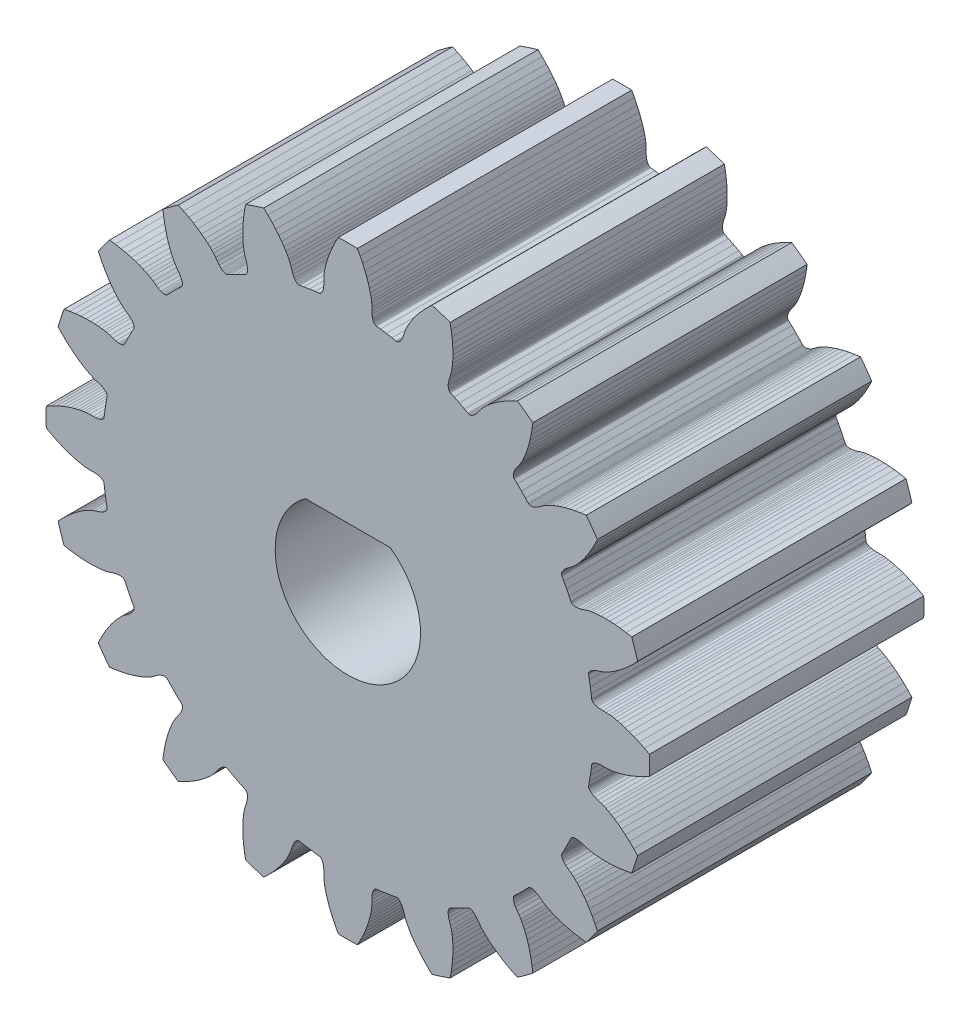
SolidWorks part; units mm, degrees
ref_plane "Front Plane" through (0, 0, 0) normal (0, 0, 1) x (1, 0, 0)
ref_plane "Top Plane" through (0, 0, 0) normal (0, 1, 0) x (1, 0, 0)
ref_plane "Right Plane" through (0, 0, 0) normal (1, 0, 0) x (0, 0, -1)
sketch "Sketch6" plane through (0, 0, 0) normal (0, 0, 1) x (1, 0, 0)
  line L0 (10.4199, 2.9158) -> (10.2643, 2.7646)
  line L1 (10.2643, 2.7646) -> (10.1156, 2.6319)
  line L2 (10.1156, 2.6319) -> (9.974, 2.5157)
  line L3 (9.974, 2.5157) -> (9.8397, 2.4145)
  line L4 (9.8397, 2.4145) -> (9.7161, 2.3294)
  line L5 (9.7161, 2.3294) -> (9.602, 2.2576)
  line L6 (9.602, 2.2576) -> (9.5009, 2.1998)
  line L7 (9.5009, 2.1998) -> (9.4118, 2.1536)
  line L8 (9.4118, 2.1536) -> (9.3359, 2.1182)
  line L9 (9.3359, 2.1182) -> (9.2232, 2.0736)
  line L10 (9.2232, 2.0736) -> (9.1099, 2.0398)
  line L11 (9.1099, 2.0398) -> (9.0055, 2.0008)
  line L12 (9.0055, 2.0008) -> (8.9204, 1.9573)
  line L13 (8.9204, 1.9573) -> (8.8851, 1.9344)
  line L14 (8.8851, 1.9344) -> (8.8547, 1.9109)
  line L15 (8.8547, 1.9109) -> (8.8292, 1.8872)
  line L16 (8.8292, 1.8872) -> (8.8085, 1.8633)
  line L17 (8.8085, 1.8633) -> (8.7927, 1.8394)
  line L18 (8.7927, 1.8394) -> (8.7818, 1.8158)
  line L19 (8.7818, 1.8158) -> (8.7757, 1.7926)
  line L20 (8.7757, 1.7926) -> (8.7744, 1.7701)
  line L21 (8.7744, 1.7701) -> (8.7765, 1.7537)
  line L22 (8.7765, 1.7537) -> (8.8045, 1.6075)
  line L23 (8.8045, 1.6075) -> (8.8398, 1.4001)
  line L24 (8.8398, 1.4001) -> (8.8703, 1.1919)
  line L25 (8.8703, 1.1919) -> (8.8889, 1.0442)
  line L26 (8.8889, 1.0442) -> (8.8919, 1.028)
  line L27 (8.8919, 1.028) -> (8.9001, 1.0069)
  line L28 (8.9001, 1.0069) -> (8.9131, 0.9868)
  line L29 (8.9131, 0.9868) -> (8.9308, 0.9677)
  line L30 (8.9308, 0.9677) -> (8.9532, 0.9499)
  line L31 (8.9532, 0.9499) -> (8.9802, 0.9335)
  line L32 (8.9802, 0.9335) -> (9.0118, 0.9188)
  line L33 (9.0118, 0.9188) -> (9.048, 0.9059)
  line L34 (9.048, 0.9059) -> (9.0886, 0.895)
  line L35 (9.0886, 0.895) -> (9.183, 0.88)
  line L36 (9.183, 0.88) -> (9.2943, 0.8751)
  line L37 (9.2943, 0.8751) -> (9.4125, 0.878)
  line L38 (9.4125, 0.878) -> (9.5335, 0.8704)
  line L39 (9.5335, 0.8704) -> (9.6166, 0.8601)
  line L40 (9.6166, 0.8601) -> (9.7157, 0.8438)
  line L41 (9.7157, 0.8438) -> (9.8297, 0.82)
  line L42 (9.8297, 0.82) -> (9.9604, 0.787)
  line L43 (9.9604, 0.787) -> (10.1042, 0.7442)
  line L44 (10.1042, 0.7442) -> (10.2632, 0.6896)
  line L45 (10.2632, 0.6896) -> (10.4339, 0.6228)
  line L46 (10.4339, 0.6228) -> (10.6162, 0.5425)
  line L47 (10.6162, 0.5425) -> (10.8109, 0.4469)
  line L48 (10.8109, 0.4469) -> (10.9945, 0.3473)
  line L49 (10.9945, -0.3473) -> (10.8109, -0.4469)
  line L50 (10.8109, -0.4469) -> (10.6162, -0.5426)
  line L51 (10.6162, -0.5426) -> (10.4338, -0.6228)
  line L52 (10.4338, -0.6228) -> (10.2632, -0.6896)
  line L53 (10.2632, -0.6896) -> (10.1042, -0.7443)
  line L54 (10.1042, -0.7443) -> (9.9604, -0.7871)
  line L55 (9.9604, -0.7871) -> (9.8297, -0.82)
  line L56 (9.8297, -0.82) -> (9.7157, -0.8438)
  line L57 (9.7157, -0.8438) -> (9.6166, -0.8602)
  line L58 (9.6166, -0.8602) -> (9.5335, -0.8704)
  line L59 (9.5335, -0.8704) -> (9.4125, -0.878)
  line L60 (9.4125, -0.878) -> (9.2943, -0.8751)
  line L61 (9.2943, -0.8751) -> (9.183, -0.88)
  line L62 (9.183, -0.88) -> (9.0886, -0.8951)
  line L63 (9.0886, -0.8951) -> (9.048, -0.9059)
  line L64 (9.048, -0.9059) -> (9.0118, -0.9188)
  line L65 (9.0118, -0.9188) -> (8.9802, -0.9336)
  line L66 (8.9802, -0.9336) -> (8.9532, -0.9499)
  line L67 (8.9532, -0.9499) -> (8.9308, -0.9677)
  line L68 (8.9308, -0.9677) -> (8.9131, -0.9868)
  line L69 (8.9131, -0.9868) -> (8.9001, -1.007)
  line L70 (8.9001, -1.007) -> (8.8919, -1.028)
  line L71 (8.8919, -1.028) -> (8.8889, -1.0443)
  line L72 (8.8889, -1.0443) -> (8.8703, -1.1919)
  line L73 (8.8703, -1.1919) -> (8.8398, -1.4001)
  line L74 (8.8398, -1.4001) -> (8.8045, -1.6075)
  line L75 (8.8045, -1.6075) -> (8.7765, -1.7537)
  line L76 (8.7765, -1.7537) -> (8.7744, -1.7701)
  line L77 (8.7744, -1.7701) -> (8.7757, -1.7926)
  line L78 (8.7757, -1.7926) -> (8.7818, -1.8158)
  line L79 (8.7818, -1.8158) -> (8.7927, -1.8394)
  line L80 (8.7927, -1.8394) -> (8.8085, -1.8633)
  line L81 (8.8085, -1.8633) -> (8.8292, -1.8872)
  line L82 (8.8292, -1.8872) -> (8.8547, -1.911)
  line L83 (8.8547, -1.911) -> (8.8851, -1.9344)
  line L84 (8.8851, -1.9344) -> (8.9204, -1.9573)
  line L85 (8.9204, -1.9573) -> (9.0055, -2.0008)
  line L86 (9.0055, -2.0008) -> (9.1099, -2.0398)
  line L87 (9.1099, -2.0398) -> (9.2232, -2.0737)
  line L88 (9.2232, -2.0737) -> (9.3358, -2.1182)
  line L89 (9.3358, -2.1182) -> (9.4118, -2.1537)
  line L90 (9.4118, -2.1537) -> (9.5009, -2.1999)
  line L91 (9.5009, -2.1999) -> (9.602, -2.2577)
  line L92 (9.602, -2.2577) -> (9.7161, -2.3294)
  line L93 (9.7161, -2.3294) -> (9.8397, -2.4146)
  line L94 (9.8397, -2.4146) -> (9.974, -2.5157)
  line L95 (9.974, -2.5157) -> (10.1156, -2.6319)
  line L96 (10.1156, -2.6319) -> (10.2643, -2.7646)
  line L97 (10.2643, -2.7646) -> (10.4199, -2.9158)
  line L98 (10.4199, -2.9158) -> (10.5637, -3.0672)
  line L99 (10.3491, -3.7278) -> (10.1437, -3.7657)
  line L100 (10.1437, -3.7657) -> (9.929, -3.7966)
  line L101 (9.929, -3.7966) -> (9.7307, -3.8166)
  line L102 (9.7307, -3.8166) -> (9.5478, -3.8274)
  line L103 (9.5478, -3.8274) -> (9.3797, -3.8302)
  line L104 (9.3797, -3.8302) -> (9.2297, -3.8264)
  line L105 (9.2297, -3.8264) -> (9.0952, -3.8174)
  line L106 (9.0952, -3.8174) -> (8.9795, -3.8048)
  line L107 (8.9795, -3.8048) -> (8.8802, -3.7897)
  line L108 (8.8802, -3.7897) -> (8.7979, -3.7738)
  line L109 (8.7979, -3.7738) -> (8.6806, -3.7436)
  line L110 (8.6806, -3.7436) -> (8.569, -3.7044)
  line L111 (8.569, -3.7044) -> (8.4616, -3.6746)
  line L112 (8.4616, -3.6746) -> (8.3672, -3.6598)
  line L113 (8.3672, -3.6598) -> (8.3252, -3.6576)
  line L114 (8.3252, -3.6576) -> (8.2868, -3.6587)
  line L115 (8.2868, -3.6587) -> (8.2522, -3.6629)
  line L116 (8.2522, -3.6629) -> (8.2214, -3.6701)
  line L117 (8.2214, -3.6701) -> (8.1946, -3.6801)
  line L118 (8.1946, -3.6801) -> (8.1719, -3.6928)
  line L119 (8.1719, -3.6928) -> (8.1534, -3.708)
  line L120 (8.1534, -3.708) -> (8.1391, -3.7254)
  line L121 (8.1391, -3.7254) -> (8.1312, -3.7399)
  line L122 (8.1312, -3.7399) -> (8.0679, -3.8746)
  line L123 (8.0679, -3.8746) -> (7.9745, -4.0632)
  line L124 (7.9745, -4.0632) -> (7.8768, -4.2496)
  line L125 (7.8768, -4.2496) -> (7.8051, -4.38)
  line L126 (7.8051, -4.38) -> (7.798, -4.3949)
  line L127 (7.798, -4.3949) -> (7.7922, -4.4167)
  line L128 (7.7922, -4.4167) -> (7.7909, -4.4406)
  line L129 (7.7909, -4.4406) -> (7.794, -4.4665)
  line L130 (7.794, -4.4665) -> (7.8016, -4.494)
  line L131 (7.8016, -4.494) -> (7.8139, -4.5232)
  line L132 (7.8139, -4.5232) -> (7.8308, -4.5537)
  line L133 (7.8308, -4.5537) -> (7.8525, -4.5854)
  line L134 (7.8525, -4.5854) -> (7.8789, -4.618)
  line L135 (7.8789, -4.618) -> (7.9465, -4.6857)
  line L136 (7.9465, -4.6857) -> (8.0337, -4.7551)
  line L137 (8.0337, -4.7551) -> (8.131, -4.8223)
  line L138 (8.131, -4.8223) -> (8.2244, -4.8995)
  line L139 (8.2244, -4.8995) -> (8.2856, -4.9566)
  line L140 (8.2856, -4.9566) -> (8.3561, -5.0281)
  line L141 (8.3561, -5.0281) -> (8.4344, -5.1143)
  line L142 (8.4344, -5.1143) -> (8.5207, -5.2178)
  line L143 (8.5207, -5.2178) -> (8.6119, -5.337)
  line L144 (8.6119, -5.337) -> (8.7085, -5.4747)
  line L145 (8.7085, -5.4747) -> (8.8073, -5.629)
  line L146 (8.8073, -5.629) -> (8.9076, -5.8011)
  line L147 (8.9076, -5.8011) -> (9.0089, -5.993)
  line L148 (9.0089, -5.993) -> (9.0989, -6.1815)
  line L149 (8.6907, -6.7434) -> (8.4836, -6.716)
  line L150 (8.4836, -6.716) -> (8.2698, -6.679)
  line L151 (8.2698, -6.679) -> (8.0751, -6.6367)
  line L152 (8.0751, -6.6367) -> (7.8978, -6.5905)
  line L153 (7.8978, -6.5905) -> (7.737, -6.5412)
  line L154 (7.737, -6.5412) -> (7.5955, -6.4913)
  line L155 (7.5955, -6.4913) -> (7.4704, -6.4411)
  line L156 (7.4704, -6.4411) -> (7.3642, -6.3934)
  line L157 (7.3642, -6.3934) -> (7.2744, -6.3484)
  line L158 (7.2744, -6.3484) -> (7.2012, -6.3078)
  line L159 (7.2012, -6.3078) -> (7.0989, -6.2428)
  line L160 (7.0989, -6.2428) -> (7.0049, -6.171)
  line L161 (7.0049, -6.171) -> (6.912, -6.1096)
  line L162 (6.912, -6.1096) -> (6.8268, -6.0663)
  line L163 (6.8268, -6.0663) -> (6.7875, -6.0512)
  line L164 (6.7875, -6.0512) -> (6.7507, -6.0404)
  line L165 (6.7507, -6.0404) -> (6.7164, -6.0337)
  line L166 (6.7164, -6.0337) -> (6.6849, -6.031)
  line L167 (6.6849, -6.031) -> (6.6564, -6.0323)
  line L168 (6.6564, -6.0323) -> (6.6308, -6.0373)
  line L169 (6.6308, -6.0373) -> (6.6085, -6.046)
  line L170 (6.6085, -6.046) -> (6.5895, -6.0582)
  line L171 (6.5895, -6.0582) -> (6.5775, -6.0696)
  line L172 (6.5775, -6.0696) -> (6.4757, -6.1781)
  line L173 (6.4757, -6.1781) -> (6.3286, -6.3286)
  line L174 (6.3286, -6.3286) -> (6.1781, -6.4757)
  line L175 (6.1781, -6.4757) -> (6.0696, -6.5775)
  line L176 (6.0696, -6.5775) -> (6.0582, -6.5895)
  line L177 (6.0582, -6.5895) -> (6.046, -6.6085)
  line L178 (6.046, -6.6085) -> (6.0373, -6.6308)
  line L179 (6.0373, -6.6308) -> (6.0323, -6.6563)
  line L180 (6.0323, -6.6563) -> (6.0311, -6.6849)
  line L181 (6.0311, -6.6849) -> (6.0337, -6.7164)
  line L182 (6.0337, -6.7164) -> (6.0404, -6.7506)
  line L183 (6.0404, -6.7506) -> (6.0512, -6.7875)
  line L184 (6.0512, -6.7875) -> (6.0663, -6.8267)
  line L185 (6.0663, -6.8267) -> (6.1096, -6.9119)
  line L186 (6.1096, -6.9119) -> (6.1711, -7.0049)
  line L187 (6.1711, -7.0049) -> (6.2428, -7.0988)
  line L188 (6.2428, -7.0988) -> (6.3078, -7.2011)
  line L189 (6.3078, -7.2011) -> (6.3484, -7.2744)
  line L190 (6.3484, -7.2744) -> (6.3934, -7.3642)
  line L191 (6.3934, -7.3642) -> (6.4412, -7.4704)
  line L192 (6.4412, -7.4704) -> (6.4913, -7.5955)
  line L193 (6.4913, -7.5955) -> (6.5412, -7.737)
  line L194 (6.5412, -7.737) -> (6.5905, -7.8978)
  line L195 (6.5905, -7.8978) -> (6.6367, -8.0751)
  line L196 (6.6367, -8.0751) -> (6.679, -8.2698)
  line L197 (6.679, -8.2698) -> (6.716, -8.4836)
  line L198 (6.716, -8.4836) -> (6.7434, -8.6906)
  line L199 (6.1815, -9.0989) -> (5.993, -9.0089)
  line L200 (5.993, -9.0089) -> (5.8011, -8.9076)
  line L201 (5.8011, -8.9076) -> (5.629, -8.8072)
  line L202 (5.629, -8.8072) -> (5.4747, -8.7085)
  line L203 (5.4747, -8.7085) -> (5.337, -8.6119)
  line L204 (5.337, -8.6119) -> (5.2178, -8.5207)
  line L205 (5.2178, -8.5207) -> (5.1143, -8.4344)
  line L206 (5.1143, -8.4344) -> (5.0281, -8.3561)
  line L207 (5.0281, -8.3561) -> (4.9566, -8.2856)
  line L208 (4.9566, -8.2856) -> (4.8995, -8.2244)
  line L209 (4.8995, -8.2244) -> (4.8223, -8.131)
  line L210 (4.8223, -8.131) -> (4.7551, -8.0337)
  line L211 (4.7551, -8.0337) -> (4.6857, -7.9464)
  line L212 (4.6857, -7.9464) -> (4.6181, -7.8789)
  line L213 (4.6181, -7.8789) -> (4.5854, -7.8525)
  line L214 (4.5854, -7.8525) -> (4.5537, -7.8308)
  line L215 (4.5537, -7.8308) -> (4.5232, -7.8139)
  line L216 (4.5232, -7.8139) -> (4.4941, -7.8016)
  line L217 (4.4941, -7.8016) -> (4.4665, -7.794)
  line L218 (4.4665, -7.794) -> (4.4406, -7.7909)
  line L219 (4.4406, -7.7909) -> (4.4167, -7.7922)
  line L220 (4.4167, -7.7922) -> (4.3949, -7.7979)
  line L221 (4.3949, -7.7979) -> (4.38, -7.8051)
  line L222 (4.38, -7.8051) -> (4.2496, -7.8768)
  line L223 (4.2496, -7.8768) -> (4.0632, -7.9745)
  line L224 (4.0632, -7.9745) -> (3.8746, -8.0679)
  line L225 (3.8746, -8.0679) -> (3.7399, -8.1312)
  line L226 (3.7399, -8.1312) -> (3.7254, -8.139)
  line L227 (3.7254, -8.139) -> (3.708, -8.1533)
  line L228 (3.708, -8.1533) -> (3.6928, -8.1719)
  line L229 (3.6928, -8.1719) -> (3.6801, -8.1946)
  line L230 (3.6801, -8.1946) -> (3.6701, -8.2214)
  line L231 (3.6701, -8.2214) -> (3.6629, -8.2522)
  line L232 (3.6629, -8.2522) -> (3.6587, -8.2868)
  line L233 (3.6587, -8.2868) -> (3.6576, -8.3252)
  line L234 (3.6576, -8.3252) -> (3.6598, -8.3672)
  line L235 (3.6598, -8.3672) -> (3.6746, -8.4616)
  line L236 (3.6746, -8.4616) -> (3.7044, -8.569)
  line L237 (3.7044, -8.569) -> (3.7436, -8.6805)
  line L238 (3.7436, -8.6805) -> (3.7738, -8.7979)
  line L239 (3.7738, -8.7979) -> (3.7897, -8.8802)
  line L240 (3.7897, -8.8802) -> (3.8048, -8.9795)
  line L241 (3.8048, -8.9795) -> (3.8174, -9.0952)
  line L242 (3.8174, -9.0952) -> (3.8264, -9.2297)
  line L243 (3.8264, -9.2297) -> (3.8302, -9.3797)
  line L244 (3.8302, -9.3797) -> (3.8274, -9.5478)
  line L245 (3.8274, -9.5478) -> (3.8166, -9.7307)
  line L246 (3.8166, -9.7307) -> (3.7966, -9.9289)
  line L247 (3.7966, -9.9289) -> (3.7657, -10.1437)
  line L248 (3.7657, -10.1437) -> (3.7278, -10.3491)
  line L249 (3.0672, -10.5637) -> (2.9158, -10.4199)
  line L250 (2.9158, -10.4199) -> (2.7646, -10.2643)
  line L251 (2.7646, -10.2643) -> (2.6319, -10.1156)
  line L252 (2.6319, -10.1156) -> (2.5157, -9.974)
  line L253 (2.5157, -9.974) -> (2.4145, -9.8397)
  line L254 (2.4145, -9.8397) -> (2.3294, -9.7161)
  line L255 (2.3294, -9.7161) -> (2.2576, -9.602)
  line L256 (2.2576, -9.602) -> (2.1999, -9.5009)
  line L257 (2.1999, -9.5009) -> (2.1537, -9.4118)
  line L258 (2.1537, -9.4118) -> (2.1182, -9.3358)
  line L259 (2.1182, -9.3358) -> (2.0736, -9.2232)
  line L260 (2.0736, -9.2232) -> (2.0398, -9.1099)
  line L261 (2.0398, -9.1099) -> (2.0008, -9.0055)
  line L262 (2.0008, -9.0055) -> (1.9573, -8.9204)
  line L263 (1.9573, -8.9204) -> (1.9344, -8.8851)
  line L264 (1.9344, -8.8851) -> (1.911, -8.8547)
  line L265 (1.911, -8.8547) -> (1.8872, -8.8292)
  line L266 (1.8872, -8.8292) -> (1.8633, -8.8085)
  line L267 (1.8633, -8.8085) -> (1.8394, -8.7927)
  line L268 (1.8394, -8.7927) -> (1.8158, -8.7818)
  line L269 (1.8158, -8.7818) -> (1.7926, -8.7757)
  line L270 (1.7926, -8.7757) -> (1.7701, -8.7744)
  line L271 (1.7701, -8.7744) -> (1.7537, -8.7765)
  line L272 (1.7537, -8.7765) -> (1.6075, -8.8045)
  line L273 (1.6075, -8.8045) -> (1.4001, -8.8398)
  line L274 (1.4001, -8.8398) -> (1.1919, -8.8703)
  line L275 (1.1919, -8.8703) -> (1.0442, -8.8889)
  line L276 (1.0442, -8.8889) -> (1.028, -8.8919)
  line L277 (1.028, -8.8919) -> (1.007, -8.9001)
  line L278 (1.007, -8.9001) -> (0.9868, -8.9131)
  line L279 (0.9868, -8.9131) -> (0.9677, -8.9308)
  line L280 (0.9677, -8.9308) -> (0.9499, -8.9532)
  line L281 (0.9499, -8.9532) -> (0.9336, -8.9802)
  line L282 (0.9336, -8.9802) -> (0.9188, -9.0118)
  line L283 (0.9188, -9.0118) -> (0.9059, -9.048)
  line L284 (0.9059, -9.048) -> (0.895, -9.0886)
  line L285 (0.895, -9.0886) -> (0.88, -9.183)
  line L286 (0.88, -9.183) -> (0.8751, -9.2943)
  line L287 (0.8751, -9.2943) -> (0.878, -9.4125)
  line L288 (0.878, -9.4125) -> (0.8704, -9.5335)
  line L289 (0.8704, -9.5335) -> (0.8602, -9.6166)
  line L290 (0.8602, -9.6166) -> (0.8438, -9.7157)
  line L291 (0.8438, -9.7157) -> (0.82, -9.8297)
  line L292 (0.82, -9.8297) -> (0.787, -9.9604)
  line L293 (0.787, -9.9604) -> (0.7443, -10.1042)
  line L294 (0.7443, -10.1042) -> (0.6896, -10.2632)
  line L295 (0.6896, -10.2632) -> (0.6228, -10.4338)
  line L296 (0.6228, -10.4338) -> (0.5425, -10.6162)
  line L297 (0.5425, -10.6162) -> (0.4469, -10.8109)
  line L298 (0.4469, -10.8109) -> (0.3473, -10.9945)
  line L299 (-0.3472, -10.9945) -> (-0.4468, -10.8109)
  line L300 (-0.4468, -10.8109) -> (-0.5425, -10.6162)
  line L301 (-0.5425, -10.6162) -> (-0.6228, -10.4338)
  line L302 (-0.6228, -10.4338) -> (-0.6896, -10.2632)
  line L303 (-0.6896, -10.2632) -> (-0.7442, -10.1042)
  line L304 (-0.7442, -10.1042) -> (-0.787, -9.9604)
  line L305 (-0.787, -9.9604) -> (-0.82, -9.8297)
  line L306 (-0.82, -9.8297) -> (-0.8437, -9.7157)
  line L307 (-0.8437, -9.7157) -> (-0.8601, -9.6166)
  line L308 (-0.8601, -9.6166) -> (-0.8704, -9.5335)
  line L309 (-0.8704, -9.5335) -> (-0.8779, -9.4125)
  line L310 (-0.8779, -9.4125) -> (-0.8751, -9.2943)
  line L311 (-0.8751, -9.2943) -> (-0.88, -9.183)
  line L312 (-0.88, -9.183) -> (-0.895, -9.0886)
  line L313 (-0.895, -9.0886) -> (-0.9059, -9.048)
  line L314 (-0.9059, -9.048) -> (-0.9188, -9.0118)
  line L315 (-0.9188, -9.0118) -> (-0.9335, -8.9802)
  line L316 (-0.9335, -8.9802) -> (-0.9499, -8.9532)
  line L317 (-0.9499, -8.9532) -> (-0.9677, -8.9308)
  line L318 (-0.9677, -8.9308) -> (-0.9868, -8.9131)
  line L319 (-0.9868, -8.9131) -> (-1.0069, -8.9001)
  line L320 (-1.0069, -8.9001) -> (-1.028, -8.8919)
  line L321 (-1.028, -8.8919) -> (-1.0442, -8.8889)
  line L322 (-1.0442, -8.8889) -> (-1.1919, -8.8703)
  line L323 (-1.1919, -8.8703) -> (-1.4001, -8.8398)
  line L324 (-1.4001, -8.8398) -> (-1.6075, -8.8045)
  line L325 (-1.6075, -8.8045) -> (-1.7537, -8.7765)
  line L326 (-1.7537, -8.7765) -> (-1.7701, -8.7744)
  line L327 (-1.7701, -8.7744) -> (-1.7926, -8.7757)
  line L328 (-1.7926, -8.7757) -> (-1.8158, -8.7818)
  line L329 (-1.8158, -8.7818) -> (-1.8394, -8.7927)
  line L330 (-1.8394, -8.7927) -> (-1.8632, -8.8085)
  line L331 (-1.8632, -8.8085) -> (-1.8871, -8.8292)
  line L332 (-1.8871, -8.8292) -> (-1.9109, -8.8547)
  line L333 (-1.9109, -8.8547) -> (-1.9344, -8.8851)
  line L334 (-1.9344, -8.8851) -> (-1.9573, -8.9204)
  line L335 (-1.9573, -8.9204) -> (-2.0008, -9.0055)
  line L336 (-2.0008, -9.0055) -> (-2.0398, -9.1099)
  line L337 (-2.0398, -9.1099) -> (-2.0736, -9.2232)
  line L338 (-2.0736, -9.2232) -> (-2.1182, -9.3358)
  line L339 (-2.1182, -9.3358) -> (-2.1536, -9.4117)
  line L340 (-2.1536, -9.4117) -> (-2.1998, -9.5009)
  line L341 (-2.1998, -9.5009) -> (-2.2576, -9.602)
  line L342 (-2.2576, -9.602) -> (-2.3294, -9.7161)
  line L343 (-2.3294, -9.7161) -> (-2.4145, -9.8397)
  line L344 (-2.4145, -9.8397) -> (-2.5156, -9.974)
  line L345 (-2.5156, -9.974) -> (-2.6319, -10.1156)
  line L346 (-2.6319, -10.1156) -> (-2.7646, -10.2643)
  line L347 (-2.7646, -10.2643) -> (-2.9157, -10.4199)
  line L348 (-2.9157, -10.4199) -> (-3.0672, -10.5637)
  line L349 (-3.7278, -10.3491) -> (-3.7657, -10.1437)
  line L350 (-3.7657, -10.1437) -> (-3.7966, -9.9289)
  line L351 (-3.7966, -9.9289) -> (-3.8166, -9.7307)
  line L352 (-3.8166, -9.7307) -> (-3.8274, -9.5478)
  line L353 (-3.8274, -9.5478) -> (-3.8302, -9.3797)
  line L354 (-3.8302, -9.3797) -> (-3.8264, -9.2296)
  line L355 (-3.8264, -9.2296) -> (-3.8174, -9.0952)
  line L356 (-3.8174, -9.0952) -> (-3.8048, -8.9794)
  line L357 (-3.8048, -8.9794) -> (-3.7897, -8.8801)
  line L358 (-3.7897, -8.8801) -> (-3.7738, -8.7979)
  line L359 (-3.7738, -8.7979) -> (-3.7436, -8.6805)
  line L360 (-3.7436, -8.6805) -> (-3.7044, -8.569)
  line L361 (-3.7044, -8.569) -> (-3.6746, -8.4616)
  line L362 (-3.6746, -8.4616) -> (-3.6598, -8.3672)
  line L363 (-3.6598, -8.3672) -> (-3.6576, -8.3252)
  line L364 (-3.6576, -8.3252) -> (-3.6587, -8.2868)
  line L365 (-3.6587, -8.2868) -> (-3.6629, -8.2522)
  line L366 (-3.6629, -8.2522) -> (-3.6701, -8.2214)
  line L367 (-3.6701, -8.2214) -> (-3.6801, -8.1946)
  line L368 (-3.6801, -8.1946) -> (-3.6928, -8.1719)
  line L369 (-3.6928, -8.1719) -> (-3.7079, -8.1533)
  line L370 (-3.7079, -8.1533) -> (-3.7254, -8.139)
  line L371 (-3.7254, -8.139) -> (-3.7399, -8.1312)
  line L372 (-3.7399, -8.1312) -> (-3.8746, -8.0679)
  line L373 (-3.8746, -8.0679) -> (-4.0632, -7.9745)
  line L374 (-4.0632, -7.9745) -> (-4.2496, -7.8768)
  line L375 (-4.2496, -7.8768) -> (-4.38, -7.8051)
  line L376 (-4.38, -7.8051) -> (-4.3949, -7.7979)
  line L377 (-4.3949, -7.7979) -> (-4.4167, -7.7922)
  line L378 (-4.4167, -7.7922) -> (-4.4406, -7.7909)
  line L379 (-4.4406, -7.7909) -> (-4.4665, -7.794)
  line L380 (-4.4665, -7.794) -> (-4.494, -7.8016)
  line L381 (-4.494, -7.8016) -> (-4.5232, -7.8139)
  line L382 (-4.5232, -7.8139) -> (-4.5537, -7.8308)
  line L383 (-4.5537, -7.8308) -> (-4.5854, -7.8525)
  line L384 (-4.5854, -7.8525) -> (-4.618, -7.8789)
  line L385 (-4.618, -7.8789) -> (-4.6857, -7.9464)
  line L386 (-4.6857, -7.9464) -> (-4.7551, -8.0336)
  line L387 (-4.7551, -8.0336) -> (-4.8223, -8.1309)
  line L388 (-4.8223, -8.1309) -> (-4.8995, -8.2243)
  line L389 (-4.8995, -8.2243) -> (-4.9566, -8.2856)
  line L390 (-4.9566, -8.2856) -> (-5.0281, -8.3561)
  line L391 (-5.0281, -8.3561) -> (-5.1143, -8.4344)
  line L392 (-5.1143, -8.4344) -> (-5.2178, -8.5207)
  line L393 (-5.2178, -8.5207) -> (-5.337, -8.6119)
  line L394 (-5.337, -8.6119) -> (-5.4747, -8.7085)
  line L395 (-5.4747, -8.7085) -> (-5.629, -8.8072)
  line L396 (-5.629, -8.8072) -> (-5.8011, -8.9076)
  line L397 (-5.8011, -8.9076) -> (-5.993, -9.0089)
  line L398 (-5.993, -9.0089) -> (-6.1815, -9.0989)
  line L399 (-6.7433, -8.6906) -> (-6.716, -8.4836)
  line L400 (-6.716, -8.4836) -> (-6.6789, -8.2698)
  line L401 (-6.6789, -8.2698) -> (-6.6367, -8.0751)
  line L402 (-6.6367, -8.0751) -> (-6.5905, -7.8978)
  line L403 (-6.5905, -7.8978) -> (-6.5412, -7.737)
  line L404 (-6.5412, -7.737) -> (-6.4913, -7.5955)
  line L405 (-6.4913, -7.5955) -> (-6.4411, -7.4704)
  line L406 (-6.4411, -7.4704) -> (-6.3933, -7.3642)
  line L407 (-6.3933, -7.3642) -> (-6.3484, -7.2744)
  line L408 (-6.3484, -7.2744) -> (-6.3078, -7.2012)
  line L409 (-6.3078, -7.2012) -> (-6.2428, -7.0988)
  line L410 (-6.2428, -7.0988) -> (-6.171, -7.0049)
  line L411 (-6.171, -7.0049) -> (-6.1095, -6.912)
  line L412 (-6.1095, -6.912) -> (-6.0662, -6.8268)
  line L413 (-6.0662, -6.8268) -> (-6.0512, -6.7875)
  line L414 (-6.0512, -6.7875) -> (-6.0404, -6.7507)
  line L415 (-6.0404, -6.7507) -> (-6.0337, -6.7164)
  line L416 (-6.0337, -6.7164) -> (-6.031, -6.6849)
  line L417 (-6.031, -6.6849) -> (-6.0323, -6.6563)
  line L418 (-6.0323, -6.6563) -> (-6.0373, -6.6308)
  line L419 (-6.0373, -6.6308) -> (-6.046, -6.6085)
  line L420 (-6.046, -6.6085) -> (-6.0582, -6.5895)
  line L421 (-6.0582, -6.5895) -> (-6.0696, -6.5775)
  line L422 (-6.0696, -6.5775) -> (-6.1781, -6.4757)
  line L423 (-6.1781, -6.4757) -> (-6.3286, -6.3286)
  line L424 (-6.3286, -6.3286) -> (-6.4757, -6.1781)
  line L425 (-6.4757, -6.1781) -> (-6.5775, -6.0696)
  line L426 (-6.5775, -6.0696) -> (-6.5895, -6.0582)
  line L427 (-6.5895, -6.0582) -> (-6.6085, -6.046)
  line L428 (-6.6085, -6.046) -> (-6.6308, -6.0373)
  line L429 (-6.6308, -6.0373) -> (-6.6563, -6.0323)
  line L430 (-6.6563, -6.0323) -> (-6.6849, -6.031)
  line L431 (-6.6849, -6.031) -> (-6.7164, -6.0337)
  line L432 (-6.7164, -6.0337) -> (-6.7506, -6.0404)
  line L433 (-6.7506, -6.0404) -> (-6.7875, -6.0512)
  line L434 (-6.7875, -6.0512) -> (-6.8267, -6.0663)
  line L435 (-6.8267, -6.0663) -> (-6.9119, -6.1096)
  line L436 (-6.9119, -6.1096) -> (-7.0049, -6.1711)
  line L437 (-7.0049, -6.1711) -> (-7.0988, -6.2428)
  line L438 (-7.0988, -6.2428) -> (-7.2011, -6.3078)
  line L439 (-7.2011, -6.3078) -> (-7.2744, -6.3484)
  line L440 (-7.2744, -6.3484) -> (-7.3642, -6.3934)
  line L441 (-7.3642, -6.3934) -> (-7.4704, -6.4412)
  line L442 (-7.4704, -6.4412) -> (-7.5955, -6.4913)
  line L443 (-7.5955, -6.4913) -> (-7.737, -6.5412)
  line L444 (-7.737, -6.5412) -> (-7.8978, -6.5905)
  line L445 (-7.8978, -6.5905) -> (-8.0751, -6.6367)
  line L446 (-8.0751, -6.6367) -> (-8.2698, -6.679)
  line L447 (-8.2698, -6.679) -> (-8.4835, -6.716)
  line L448 (-8.4835, -6.716) -> (-8.6906, -6.7434)
  line L449 (-9.0988, -6.1815) -> (-9.0089, -5.993)
  line L450 (-9.0089, -5.993) -> (-8.9076, -5.8011)
  line L451 (-8.9076, -5.8011) -> (-8.8072, -5.629)
  line L452 (-8.8072, -5.629) -> (-8.7084, -5.4747)
  line L453 (-8.7084, -5.4747) -> (-8.6119, -5.337)
  line L454 (-8.6119, -5.337) -> (-8.5207, -5.2178)
  line L455 (-8.5207, -5.2178) -> (-8.4343, -5.1143)
  line L456 (-8.4343, -5.1143) -> (-8.3561, -5.0281)
  line L457 (-8.3561, -5.0281) -> (-8.2856, -4.9566)
  line L458 (-8.2856, -4.9566) -> (-8.2243, -4.8995)
  line L459 (-8.2243, -4.8995) -> (-8.1309, -4.8223)
  line L460 (-8.1309, -4.8223) -> (-8.0336, -4.7551)
  line L461 (-8.0336, -4.7551) -> (-7.9464, -4.6857)
  line L462 (-7.9464, -4.6857) -> (-7.8789, -4.6181)
  line L463 (-7.8789, -4.6181) -> (-7.8525, -4.5854)
  line L464 (-7.8525, -4.5854) -> (-7.8308, -4.5537)
  line L465 (-7.8308, -4.5537) -> (-7.8139, -4.5232)
  line L466 (-7.8139, -4.5232) -> (-7.8016, -4.4941)
  line L467 (-7.8016, -4.4941) -> (-7.7939, -4.4665)
  line L468 (-7.7939, -4.4665) -> (-7.7908, -4.4407)
  line L469 (-7.7908, -4.4407) -> (-7.7922, -4.4167)
  line L470 (-7.7922, -4.4167) -> (-7.7979, -4.3949)
  line L471 (-7.7979, -4.3949) -> (-7.805, -4.38)
  line L472 (-7.805, -4.38) -> (-7.8768, -4.2496)
  line L473 (-7.8768, -4.2496) -> (-7.9745, -4.0632)
  line L474 (-7.9745, -4.0632) -> (-8.0679, -3.8747)
  line L475 (-8.0679, -3.8747) -> (-8.1311, -3.74)
  line L476 (-8.1311, -3.74) -> (-8.139, -3.7254)
  line L477 (-8.139, -3.7254) -> (-8.1533, -3.708)
  line L478 (-8.1533, -3.708) -> (-8.1719, -3.6928)
  line L479 (-8.1719, -3.6928) -> (-8.1946, -3.6801)
  line L480 (-8.1946, -3.6801) -> (-8.2214, -3.6701)
  line L481 (-8.2214, -3.6701) -> (-8.2522, -3.6629)
  line L482 (-8.2522, -3.6629) -> (-8.2868, -3.6587)
  line L483 (-8.2868, -3.6587) -> (-8.3252, -3.6576)
  line L484 (-8.3252, -3.6576) -> (-8.3672, -3.6598)
  line L485 (-8.3672, -3.6598) -> (-8.4616, -3.6746)
  line L486 (-8.4616, -3.6746) -> (-8.569, -3.7044)
  line L487 (-8.569, -3.7044) -> (-8.6805, -3.7436)
  line L488 (-8.6805, -3.7436) -> (-8.7979, -3.7738)
  line L489 (-8.7979, -3.7738) -> (-8.8801, -3.7898)
  line L490 (-8.8801, -3.7898) -> (-8.9794, -3.8048)
  line L491 (-8.9794, -3.8048) -> (-9.0951, -3.8174)
  line L492 (-9.0951, -3.8174) -> (-9.2296, -3.8265)
  line L493 (-9.2296, -3.8265) -> (-9.3797, -3.8302)
  line L494 (-9.3797, -3.8302) -> (-9.5478, -3.8274)
  line L495 (-9.5478, -3.8274) -> (-9.7307, -3.8166)
  line L496 (-9.7307, -3.8166) -> (-9.9289, -3.7966)
  line L497 (-9.9289, -3.7966) -> (-10.1437, -3.7658)
  line L498 (-10.1437, -3.7658) -> (-10.3491, -3.7278)
  line L499 (-10.5637, -3.0672) -> (-10.4199, -2.9158)
  line L500 (-10.4199, -2.9158) -> (-10.2642, -2.7646)
  line L501 (-10.2642, -2.7646) -> (-10.1156, -2.6319)
  line L502 (-10.1156, -2.6319) -> (-9.974, -2.5157)
  line L503 (-9.974, -2.5157) -> (-9.8396, -2.4145)
  line L504 (-9.8396, -2.4145) -> (-9.7161, -2.3294)
  line L505 (-9.7161, -2.3294) -> (-9.602, -2.2576)
  line L506 (-9.602, -2.2576) -> (-9.5009, -2.1998)
  line L507 (-9.5009, -2.1998) -> (-9.4117, -2.1536)
  line L508 (-9.4117, -2.1536) -> (-9.3358, -2.1182)
  line L509 (-9.3358, -2.1182) -> (-9.2231, -2.0736)
  line L510 (-9.2231, -2.0736) -> (-9.1098, -2.0398)
  line L511 (-9.1098, -2.0398) -> (-9.0055, -2.0008)
  line L512 (-9.0055, -2.0008) -> (-8.9204, -1.9573)
  line L513 (-8.9204, -1.9573) -> (-8.8851, -1.9344)
  line L514 (-8.8851, -1.9344) -> (-8.8547, -1.9109)
  line L515 (-8.8547, -1.9109) -> (-8.8292, -1.8872)
  line L516 (-8.8292, -1.8872) -> (-8.8085, -1.8633)
  line L517 (-8.8085, -1.8633) -> (-8.7927, -1.8394)
  line L518 (-8.7927, -1.8394) -> (-8.7818, -1.8158)
  line L519 (-8.7818, -1.8158) -> (-8.7757, -1.7926)
  line L520 (-8.7757, -1.7926) -> (-8.7744, -1.7701)
  line L521 (-8.7744, -1.7701) -> (-8.7765, -1.7537)
  line L522 (-8.7765, -1.7537) -> (-8.8045, -1.6075)
  line L523 (-8.8045, -1.6075) -> (-8.8398, -1.4001)
  line L524 (-8.8398, -1.4001) -> (-8.8703, -1.1919)
  line L525 (-8.8703, -1.1919) -> (-8.8889, -1.0442)
  line L526 (-8.8889, -1.0442) -> (-8.8919, -1.028)
  line L527 (-8.8919, -1.028) -> (-8.9001, -1.0069)
  line L528 (-8.9001, -1.0069) -> (-8.9131, -0.9868)
  line L529 (-8.9131, -0.9868) -> (-8.9308, -0.9677)
  line L530 (-8.9308, -0.9677) -> (-8.9532, -0.9499)
  line L531 (-8.9532, -0.9499) -> (-8.9802, -0.9336)
  line L532 (-8.9802, -0.9336) -> (-9.0118, -0.9188)
  line L533 (-9.0118, -0.9188) -> (-9.048, -0.9059)
  line L534 (-9.048, -0.9059) -> (-9.0886, -0.895)
  line L535 (-9.0886, -0.895) -> (-9.183, -0.88)
  line L536 (-9.183, -0.88) -> (-9.2943, -0.8751)
  line L537 (-9.2943, -0.8751) -> (-9.4125, -0.878)
  line L538 (-9.4125, -0.878) -> (-9.5335, -0.8704)
  line L539 (-9.5335, -0.8704) -> (-9.6166, -0.8601)
  line L540 (-9.6166, -0.8601) -> (-9.7157, -0.8438)
  line L541 (-9.7157, -0.8438) -> (-9.8297, -0.82)
  line L542 (-9.8297, -0.82) -> (-9.9603, -0.787)
  line L543 (-9.9603, -0.787) -> (-10.1042, -0.7443)
  line L544 (-10.1042, -0.7443) -> (-10.2632, -0.6896)
  line L545 (-10.2632, -0.6896) -> (-10.4338, -0.6228)
  line L546 (-10.4338, -0.6228) -> (-10.6162, -0.5425)
  line L547 (-10.6162, -0.5425) -> (-10.8109, -0.4469)
  line L548 (-10.8109, -0.4469) -> (-10.9945, -0.3473)
  line L549 (-10.9945, 0.3473) -> (-10.8109, 0.4469)
  line L550 (-10.8109, 0.4469) -> (-10.6162, 0.5425)
  line L551 (-10.6162, 0.5425) -> (-10.4338, 0.6228)
  line L552 (-10.4338, 0.6228) -> (-10.2632, 0.6896)
  line L553 (-10.2632, 0.6896) -> (-10.1042, 0.7443)
  line L554 (-10.1042, 0.7443) -> (-9.9603, 0.787)
  line L555 (-9.9603, 0.787) -> (-9.8297, 0.82)
  line L556 (-9.8297, 0.82) -> (-9.7157, 0.8438)
  line L557 (-9.7157, 0.8438) -> (-9.6166, 0.8602)
  line L558 (-9.6166, 0.8602) -> (-9.5335, 0.8704)
  line L559 (-9.5335, 0.8704) -> (-9.4125, 0.878)
  line L560 (-9.4125, 0.878) -> (-9.2943, 0.8751)
  line L561 (-9.2943, 0.8751) -> (-9.183, 0.88)
  line L562 (-9.183, 0.88) -> (-9.0886, 0.895)
  line L563 (-9.0886, 0.895) -> (-9.048, 0.9059)
  line L564 (-9.048, 0.9059) -> (-9.0118, 0.9188)
  line L565 (-9.0118, 0.9188) -> (-8.9802, 0.9336)
  line L566 (-8.9802, 0.9336) -> (-8.9532, 0.9499)
  line L567 (-8.9532, 0.9499) -> (-8.9308, 0.9677)
  line L568 (-8.9308, 0.9677) -> (-8.9131, 0.9868)
  line L569 (-8.9131, 0.9868) -> (-8.9001, 1.007)
  line L570 (-8.9001, 1.007) -> (-8.8919, 1.028)
  line L571 (-8.8919, 1.028) -> (-8.8889, 1.0442)
  line L572 (-8.8889, 1.0442) -> (-8.8703, 1.1919)
  line L573 (-8.8703, 1.1919) -> (-8.8398, 1.4001)
  line L574 (-8.8398, 1.4001) -> (-8.8045, 1.6075)
  line L575 (-8.8045, 1.6075) -> (-8.7765, 1.7537)
  line L576 (-8.7765, 1.7537) -> (-8.7744, 1.7701)
  line L577 (-8.7744, 1.7701) -> (-8.7757, 1.7926)
  line L578 (-8.7757, 1.7926) -> (-8.7818, 1.8158)
  line L579 (-8.7818, 1.8158) -> (-8.7927, 1.8394)
  line L580 (-8.7927, 1.8394) -> (-8.8085, 1.8633)
  line L581 (-8.8085, 1.8633) -> (-8.8292, 1.8872)
  line L582 (-8.8292, 1.8872) -> (-8.8547, 1.9109)
  line L583 (-8.8547, 1.9109) -> (-8.8851, 1.9344)
  line L584 (-8.8851, 1.9344) -> (-8.9204, 1.9573)
  line L585 (-8.9204, 1.9573) -> (-9.0055, 2.0008)
  line L586 (-9.0055, 2.0008) -> (-9.1098, 2.0398)
  line L587 (-9.1098, 2.0398) -> (-9.2231, 2.0736)
  line L588 (-9.2231, 2.0736) -> (-9.3358, 2.1182)
  line L589 (-9.3358, 2.1182) -> (-9.4117, 2.1536)
  line L590 (-9.4117, 2.1536) -> (-9.5009, 2.1999)
  line L591 (-9.5009, 2.1999) -> (-9.602, 2.2576)
  line L592 (-9.602, 2.2576) -> (-9.7161, 2.3294)
  line L593 (-9.7161, 2.3294) -> (-9.8396, 2.4145)
  line L594 (-9.8396, 2.4145) -> (-9.974, 2.5157)
  line L595 (-9.974, 2.5157) -> (-10.1156, 2.6319)
  line L596 (-10.1156, 2.6319) -> (-10.2642, 2.7646)
  line L597 (-10.2642, 2.7646) -> (-10.4199, 2.9158)
  line L598 (-10.4199, 2.9158) -> (-10.5637, 3.0672)
  line L599 (-10.3491, 3.7278) -> (-10.1437, 3.7657)
  line L600 (-10.1437, 3.7657) -> (-9.9289, 3.7966)
  line L601 (-9.9289, 3.7966) -> (-9.7307, 3.8166)
  line L602 (-9.7307, 3.8166) -> (-9.5478, 3.8274)
  line L603 (-9.5478, 3.8274) -> (-9.3797, 3.8302)
  line L604 (-9.3797, 3.8302) -> (-9.2296, 3.8264)
  line L605 (-9.2296, 3.8264) -> (-9.0952, 3.8174)
  line L606 (-9.0952, 3.8174) -> (-8.9794, 3.8048)
  line L607 (-8.9794, 3.8048) -> (-8.8801, 3.7897)
  line L608 (-8.8801, 3.7897) -> (-8.7979, 3.7738)
  line L609 (-8.7979, 3.7738) -> (-8.6805, 3.7436)
  line L610 (-8.6805, 3.7436) -> (-8.569, 3.7044)
  line L611 (-8.569, 3.7044) -> (-8.4616, 3.6746)
  line L612 (-8.4616, 3.6746) -> (-8.3672, 3.6598)
  line L613 (-8.3672, 3.6598) -> (-8.3252, 3.6576)
  line L614 (-8.3252, 3.6576) -> (-8.2868, 3.6587)
  line L615 (-8.2868, 3.6587) -> (-8.2522, 3.6629)
  line L616 (-8.2522, 3.6629) -> (-8.2214, 3.6701)
  line L617 (-8.2214, 3.6701) -> (-8.1946, 3.6801)
  line L618 (-8.1946, 3.6801) -> (-8.1719, 3.6928)
  line L619 (-8.1719, 3.6928) -> (-8.1533, 3.7079)
  line L620 (-8.1533, 3.7079) -> (-8.139, 3.7254)
  line L621 (-8.139, 3.7254) -> (-8.1311, 3.7399)
  line L622 (-8.1311, 3.7399) -> (-8.0679, 3.8746)
  line L623 (-8.0679, 3.8746) -> (-7.9745, 4.0632)
  line L624 (-7.9745, 4.0632) -> (-7.8768, 4.2496)
  line L625 (-7.8768, 4.2496) -> (-7.805, 4.38)
  line L626 (-7.805, 4.38) -> (-7.7979, 4.3949)
  line L627 (-7.7979, 4.3949) -> (-7.7922, 4.4167)
  line L628 (-7.7922, 4.4167) -> (-7.7908, 4.4406)
  line L629 (-7.7908, 4.4406) -> (-7.794, 4.4665)
  line L630 (-7.794, 4.4665) -> (-7.8016, 4.494)
  line L631 (-7.8016, 4.494) -> (-7.8139, 4.5232)
  line L632 (-7.8139, 4.5232) -> (-7.8308, 4.5537)
  line L633 (-7.8308, 4.5537) -> (-7.8525, 4.5854)
  line L634 (-7.8525, 4.5854) -> (-7.8789, 4.618)
  line L635 (-7.8789, 4.618) -> (-7.9464, 4.6857)
  line L636 (-7.9464, 4.6857) -> (-8.0336, 4.7551)
  line L637 (-8.0336, 4.7551) -> (-8.1309, 4.8223)
  line L638 (-8.1309, 4.8223) -> (-8.2243, 4.8995)
  line L639 (-8.2243, 4.8995) -> (-8.2856, 4.9566)
  line L640 (-8.2856, 4.9566) -> (-8.3561, 5.0281)
  line L641 (-8.3561, 5.0281) -> (-8.4344, 5.1143)
  line L642 (-8.4344, 5.1143) -> (-8.5207, 5.2178)
  line L643 (-8.5207, 5.2178) -> (-8.6119, 5.337)
  line L644 (-8.6119, 5.337) -> (-8.7084, 5.4747)
  line L645 (-8.7084, 5.4747) -> (-8.8072, 5.629)
  line L646 (-8.8072, 5.629) -> (-8.9076, 5.8011)
  line L647 (-8.9076, 5.8011) -> (-9.0089, 5.993)
  line L648 (-9.0089, 5.993) -> (-9.0989, 6.1815)
  line L649 (-8.6906, 6.7434) -> (-8.4835, 6.716)
  line L650 (-8.4835, 6.716) -> (-8.2698, 6.679)
  line L651 (-8.2698, 6.679) -> (-8.075, 6.6367)
  line L652 (-8.075, 6.6367) -> (-7.8978, 6.5905)
  line L653 (-7.8978, 6.5905) -> (-7.737, 6.5412)
  line L654 (-7.737, 6.5412) -> (-7.5955, 6.4913)
  line L655 (-7.5955, 6.4913) -> (-7.4703, 6.4411)
  line L656 (-7.4703, 6.4411) -> (-7.3642, 6.3934)
  line L657 (-7.3642, 6.3934) -> (-7.2744, 6.3484)
  line L658 (-7.2744, 6.3484) -> (-7.2011, 6.3078)
  line L659 (-7.2011, 6.3078) -> (-7.0988, 6.2428)
  line L660 (-7.0988, 6.2428) -> (-7.0049, 6.1711)
  line L661 (-7.0049, 6.1711) -> (-6.9119, 6.1096)
  line L662 (-6.9119, 6.1096) -> (-6.8267, 6.0663)
  line L663 (-6.8267, 6.0663) -> (-6.7875, 6.0512)
  line L664 (-6.7875, 6.0512) -> (-6.7506, 6.0404)
  line L665 (-6.7506, 6.0404) -> (-6.7164, 6.0337)
  line L666 (-6.7164, 6.0337) -> (-6.6849, 6.031)
  line L667 (-6.6849, 6.031) -> (-6.6563, 6.0323)
  line L668 (-6.6563, 6.0323) -> (-6.6308, 6.0373)
  line L669 (-6.6308, 6.0373) -> (-6.6084, 6.046)
  line L670 (-6.6084, 6.046) -> (-6.5894, 6.0582)
  line L671 (-6.5894, 6.0582) -> (-6.5775, 6.0696)
  line L672 (-6.5775, 6.0696) -> (-6.4757, 6.1781)
  line L673 (-6.4757, 6.1781) -> (-6.3286, 6.3286)
  line L674 (-6.3286, 6.3286) -> (-6.1781, 6.4757)
  line L675 (-6.1781, 6.4757) -> (-6.0695, 6.5775)
  line L676 (-6.0695, 6.5775) -> (-6.0582, 6.5895)
  line L677 (-6.0582, 6.5895) -> (-6.046, 6.6085)
  line L678 (-6.046, 6.6085) -> (-6.0373, 6.6308)
  line L679 (-6.0373, 6.6308) -> (-6.0323, 6.6563)
  line L680 (-6.0323, 6.6563) -> (-6.031, 6.6849)
  line L681 (-6.031, 6.6849) -> (-6.0337, 6.7164)
  line L682 (-6.0337, 6.7164) -> (-6.0403, 6.7506)
  line L683 (-6.0403, 6.7506) -> (-6.0512, 6.7875)
  line L684 (-6.0512, 6.7875) -> (-6.0662, 6.8268)
  line L685 (-6.0662, 6.8268) -> (-6.1095, 6.912)
  line L686 (-6.1095, 6.912) -> (-6.171, 7.0049)
  line L687 (-6.171, 7.0049) -> (-6.2428, 7.0988)
  line L688 (-6.2428, 7.0988) -> (-6.3078, 7.2012)
  line L689 (-6.3078, 7.2012) -> (-6.3484, 7.2744)
  line L690 (-6.3484, 7.2744) -> (-6.3933, 7.3642)
  line L691 (-6.3933, 7.3642) -> (-6.4411, 7.4704)
  line L692 (-6.4411, 7.4704) -> (-6.4913, 7.5955)
  line L693 (-6.4913, 7.5955) -> (-6.5412, 7.737)
  line L694 (-6.5412, 7.737) -> (-6.5905, 7.8978)
  line L695 (-6.5905, 7.8978) -> (-6.6367, 8.0751)
  line L696 (-6.6367, 8.0751) -> (-6.6789, 8.2698)
  line L697 (-6.6789, 8.2698) -> (-6.716, 8.4836)
  line L698 (-6.716, 8.4836) -> (-6.7433, 8.6906)
  line L699 (-6.1815, 9.0989) -> (-5.993, 9.0089)
  line L700 (-5.993, 9.0089) -> (-5.8011, 8.9076)
  line L701 (-5.8011, 8.9076) -> (-5.629, 8.8072)
  line L702 (-5.629, 8.8072) -> (-5.4747, 8.7085)
  line L703 (-5.4747, 8.7085) -> (-5.337, 8.6119)
  line L704 (-5.337, 8.6119) -> (-5.2178, 8.5207)
  line L705 (-5.2178, 8.5207) -> (-5.1143, 8.4344)
  line L706 (-5.1143, 8.4344) -> (-5.0281, 8.3561)
  line L707 (-5.0281, 8.3561) -> (-4.9566, 8.2856)
  line L708 (-4.9566, 8.2856) -> (-4.8995, 8.2243)
  line L709 (-4.8995, 8.2243) -> (-4.8222, 8.1309)
  line L710 (-4.8222, 8.1309) -> (-4.7551, 8.0336)
  line L711 (-4.7551, 8.0336) -> (-4.6857, 7.9464)
  line L712 (-4.6857, 7.9464) -> (-4.618, 7.8789)
  line L713 (-4.618, 7.8789) -> (-4.5853, 7.8525)
  line L714 (-4.5853, 7.8525) -> (-4.5536, 7.8308)
  line L715 (-4.5536, 7.8308) -> (-4.5231, 7.8139)
  line L716 (-4.5231, 7.8139) -> (-4.494, 7.8016)
  line L717 (-4.494, 7.8016) -> (-4.4665, 7.794)
  line L718 (-4.4665, 7.794) -> (-4.4406, 7.7909)
  line L719 (-4.4406, 7.7909) -> (-4.4167, 7.7922)
  line L720 (-4.4167, 7.7922) -> (-4.3949, 7.7979)
  line L721 (-4.3949, 7.7979) -> (-4.3799, 7.8051)
  line L722 (-4.3799, 7.8051) -> (-4.2496, 7.8768)
  line L723 (-4.2496, 7.8768) -> (-4.0632, 7.9745)
  line L724 (-4.0632, 7.9745) -> (-3.8746, 8.0679)
  line L725 (-3.8746, 8.0679) -> (-3.7399, 8.1312)
  line L726 (-3.7399, 8.1312) -> (-3.7254, 8.139)
  line L727 (-3.7254, 8.139) -> (-3.7079, 8.1533)
  line L728 (-3.7079, 8.1533) -> (-3.6928, 8.1719)
  line L729 (-3.6928, 8.1719) -> (-3.6801, 8.1946)
  line L730 (-3.6801, 8.1946) -> (-3.6701, 8.2214)
  line L731 (-3.6701, 8.2214) -> (-3.6629, 8.2522)
  line L732 (-3.6629, 8.2522) -> (-3.6587, 8.2868)
  line L733 (-3.6587, 8.2868) -> (-3.6576, 8.3252)
  line L734 (-3.6576, 8.3252) -> (-3.6598, 8.3672)
  line L735 (-3.6598, 8.3672) -> (-3.6746, 8.4616)
  line L736 (-3.6746, 8.4616) -> (-3.7044, 8.569)
  line L737 (-3.7044, 8.569) -> (-3.7436, 8.6805)
  line L738 (-3.7436, 8.6805) -> (-3.7738, 8.7979)
  line L739 (-3.7738, 8.7979) -> (-3.7897, 8.8801)
  line L740 (-3.7897, 8.8801) -> (-3.8048, 8.9794)
  line L741 (-3.8048, 8.9794) -> (-3.8174, 9.0952)
  line L742 (-3.8174, 9.0952) -> (-3.8264, 9.2296)
  line L743 (-3.8264, 9.2296) -> (-3.8302, 9.3797)
  line L744 (-3.8302, 9.3797) -> (-3.8273, 9.5478)
  line L745 (-3.8273, 9.5478) -> (-3.8166, 9.7307)
  line L746 (-3.8166, 9.7307) -> (-3.7965, 9.9289)
  line L747 (-3.7965, 9.9289) -> (-3.7657, 10.1437)
  line L748 (-3.7657, 10.1437) -> (-3.7277, 10.3491)
  line L749 (-3.0672, 10.5637) -> (-2.9158, 10.4199)
  line L750 (-2.9158, 10.4199) -> (-2.7646, 10.2642)
  line L751 (-2.7646, 10.2642) -> (-2.6319, 10.1156)
  line L752 (-2.6319, 10.1156) -> (-2.5157, 9.974)
  line L753 (-2.5157, 9.974) -> (-2.4145, 9.8396)
  line L754 (-2.4145, 9.8396) -> (-2.3294, 9.7161)
  line L755 (-2.3294, 9.7161) -> (-2.2576, 9.602)
  line L756 (-2.2576, 9.602) -> (-2.1999, 9.5009)
  line L757 (-2.1999, 9.5009) -> (-2.1536, 9.4117)
  line L758 (-2.1536, 9.4117) -> (-2.1182, 9.3358)
  line L759 (-2.1182, 9.3358) -> (-2.0736, 9.2231)
  line L760 (-2.0736, 9.2231) -> (-2.0398, 9.1098)
  line L761 (-2.0398, 9.1098) -> (-2.0008, 9.0055)
  line L762 (-2.0008, 9.0055) -> (-1.9573, 8.9204)
  line L763 (-1.9573, 8.9204) -> (-1.9344, 8.8851)
  line L764 (-1.9344, 8.8851) -> (-1.9109, 8.8547)
  line L765 (-1.9109, 8.8547) -> (-1.8872, 8.8292)
  line L766 (-1.8872, 8.8292) -> (-1.8633, 8.8085)
  line L767 (-1.8633, 8.8085) -> (-1.8394, 8.7927)
  line L768 (-1.8394, 8.7927) -> (-1.8158, 8.7818)
  line L769 (-1.8158, 8.7818) -> (-1.7926, 8.7757)
  line L770 (-1.7926, 8.7757) -> (-1.7701, 8.7744)
  line L771 (-1.7701, 8.7744) -> (-1.7537, 8.7765)
  line L772 (-1.7537, 8.7765) -> (-1.6075, 8.8045)
  line L773 (-1.6075, 8.8045) -> (-1.4001, 8.8398)
  line L774 (-1.4001, 8.8398) -> (-1.1919, 8.8703)
  line L775 (-1.1919, 8.8703) -> (-1.0442, 8.8889)
  line L776 (-1.0442, 8.8889) -> (-1.028, 8.8919)
  line L777 (-1.028, 8.8919) -> (-1.0069, 8.9001)
  line L778 (-1.0069, 8.9001) -> (-0.9868, 8.9131)
  line L779 (-0.9868, 8.9131) -> (-0.9677, 8.9308)
  line L780 (-0.9677, 8.9308) -> (-0.9499, 8.9532)
  line L781 (-0.9499, 8.9532) -> (-0.9336, 8.9802)
  line L782 (-0.9336, 8.9802) -> (-0.9188, 9.0118)
  line L783 (-0.9188, 9.0118) -> (-0.9059, 9.048)
  line L784 (-0.9059, 9.048) -> (-0.895, 9.0886)
  line L785 (-0.895, 9.0886) -> (-0.88, 9.183)
  line L786 (-0.88, 9.183) -> (-0.8751, 9.2943)
  line L787 (-0.8751, 9.2943) -> (-0.878, 9.4125)
  line L788 (-0.878, 9.4125) -> (-0.8704, 9.5335)
  line L789 (-0.8704, 9.5335) -> (-0.8601, 9.6166)
  line L790 (-0.8601, 9.6166) -> (-0.8438, 9.7157)
  line L791 (-0.8438, 9.7157) -> (-0.82, 9.8297)
  line L792 (-0.82, 9.8297) -> (-0.787, 9.9603)
  line L793 (-0.787, 9.9603) -> (-0.7443, 10.1042)
  line L794 (-0.7443, 10.1042) -> (-0.6896, 10.2632)
  line L795 (-0.6896, 10.2632) -> (-0.6228, 10.4338)
  line L796 (-0.6228, 10.4338) -> (-0.5425, 10.6162)
  line L797 (-0.5425, 10.6162) -> (-0.4469, 10.8109)
  line L798 (-0.4469, 10.8109) -> (-0.3473, 10.9945)
  line L799 (0.3473, 10.9945) -> (0.4469, 10.8109)
  line L800 (0.4469, 10.8109) -> (0.5425, 10.6162)
  line L801 (0.5425, 10.6162) -> (0.6228, 10.4338)
  line L802 (0.6228, 10.4338) -> (0.6896, 10.2632)
  line L803 (0.6896, 10.2632) -> (0.7443, 10.1042)
  line L804 (0.7443, 10.1042) -> (0.7871, 9.9603)
  line L805 (0.7871, 9.9603) -> (0.82, 9.8297)
  line L806 (0.82, 9.8297) -> (0.8438, 9.7157)
  line L807 (0.8438, 9.7157) -> (0.8602, 9.6166)
  line L808 (0.8602, 9.6166) -> (0.8704, 9.5335)
  line L809 (0.8704, 9.5335) -> (0.878, 9.4125)
  line L810 (0.878, 9.4125) -> (0.8751, 9.2943)
  line L811 (0.8751, 9.2943) -> (0.88, 9.183)
  line L812 (0.88, 9.183) -> (0.8951, 9.0886)
  line L813 (0.8951, 9.0886) -> (0.9059, 9.048)
  line L814 (0.9059, 9.048) -> (0.9188, 9.0118)
  line L815 (0.9188, 9.0118) -> (0.9336, 8.9802)
  line L816 (0.9336, 8.9802) -> (0.9499, 8.9532)
  line L817 (0.9499, 8.9532) -> (0.9677, 8.9308)
  line L818 (0.9677, 8.9308) -> (0.9868, 8.9131)
  line L819 (0.9868, 8.9131) -> (1.007, 8.9001)
  line L820 (1.007, 8.9001) -> (1.028, 8.8919)
  line L821 (1.028, 8.8919) -> (1.0442, 8.8889)
  line L822 (1.0442, 8.8889) -> (1.1919, 8.8703)
  line L823 (1.1919, 8.8703) -> (1.4001, 8.8398)
  line L824 (1.4001, 8.8398) -> (1.6075, 8.8045)
  line L825 (1.6075, 8.8045) -> (1.7537, 8.7765)
  line L826 (1.7537, 8.7765) -> (1.7701, 8.7744)
  line L827 (1.7701, 8.7744) -> (1.7926, 8.7757)
  line L828 (1.7926, 8.7757) -> (1.8158, 8.7818)
  line L829 (1.8158, 8.7818) -> (1.8394, 8.7927)
  line L830 (1.8394, 8.7927) -> (1.8633, 8.8085)
  line L831 (1.8633, 8.8085) -> (1.8872, 8.8292)
  line L832 (1.8872, 8.8292) -> (1.911, 8.8547)
  line L833 (1.911, 8.8547) -> (1.9344, 8.8851)
  line L834 (1.9344, 8.8851) -> (1.9573, 8.9204)
  line L835 (1.9573, 8.9204) -> (2.0008, 9.0055)
  line L836 (2.0008, 9.0055) -> (2.0398, 9.1098)
  line L837 (2.0398, 9.1098) -> (2.0736, 9.2231)
  line L838 (2.0736, 9.2231) -> (2.1182, 9.3358)
  line L839 (2.1182, 9.3358) -> (2.1537, 9.4117)
  line L840 (2.1537, 9.4117) -> (2.1999, 9.5009)
  line L841 (2.1999, 9.5009) -> (2.2577, 9.602)
  line L842 (2.2577, 9.602) -> (2.3294, 9.7161)
  line L843 (2.3294, 9.7161) -> (2.4145, 9.8396)
  line L844 (2.4145, 9.8396) -> (2.5157, 9.974)
  line L845 (2.5157, 9.974) -> (2.6319, 10.1156)
  line L846 (2.6319, 10.1156) -> (2.7646, 10.2642)
  line L847 (2.7646, 10.2642) -> (2.9158, 10.4199)
  line L848 (2.9158, 10.4199) -> (3.0672, 10.5637)
  line L849 (3.7278, 10.3491) -> (3.7658, 10.1437)
  line L850 (3.7658, 10.1437) -> (3.7966, 9.9289)
  line L851 (3.7966, 9.9289) -> (3.8166, 9.7307)
  line L852 (3.8166, 9.7307) -> (3.8274, 9.5478)
  line L853 (3.8274, 9.5478) -> (3.8302, 9.3797)
  line L854 (3.8302, 9.3797) -> (3.8264, 9.2296)
  line L855 (3.8264, 9.2296) -> (3.8174, 9.0952)
  line L856 (3.8174, 9.0952) -> (3.8048, 8.9794)
  line L857 (3.8048, 8.9794) -> (3.7898, 8.8801)
  line L858 (3.7898, 8.8801) -> (3.7738, 8.7979)
  line L859 (3.7738, 8.7979) -> (3.7436, 8.6805)
  line L860 (3.7436, 8.6805) -> (3.7044, 8.569)
  line L861 (3.7044, 8.569) -> (3.6746, 8.4616)
  line L862 (3.6746, 8.4616) -> (3.6598, 8.3672)
  line L863 (3.6598, 8.3672) -> (3.6576, 8.3252)
  line L864 (3.6576, 8.3252) -> (3.6587, 8.2868)
  line L865 (3.6587, 8.2868) -> (3.6629, 8.2522)
  line L866 (3.6629, 8.2522) -> (3.6701, 8.2214)
  line L867 (3.6701, 8.2214) -> (3.6801, 8.1946)
  line L868 (3.6801, 8.1946) -> (3.6928, 8.1719)
  line L869 (3.6928, 8.1719) -> (3.708, 8.1533)
  line L870 (3.708, 8.1533) -> (3.7254, 8.139)
  line L871 (3.7254, 8.139) -> (3.74, 8.1312)
  line L872 (3.74, 8.1312) -> (3.8746, 8.0679)
  line L873 (3.8746, 8.0679) -> (4.0632, 7.9745)
  line L874 (4.0632, 7.9745) -> (4.2496, 7.8768)
  line L875 (4.2496, 7.8768) -> (4.38, 7.8051)
  line L876 (4.38, 7.8051) -> (4.3949, 7.7979)
  line L877 (4.3949, 7.7979) -> (4.4167, 7.7922)
  line L878 (4.4167, 7.7922) -> (4.4406, 7.7909)
  line L879 (4.4406, 7.7909) -> (4.4665, 7.794)
  line L880 (4.4665, 7.794) -> (4.4941, 7.8016)
  line L881 (4.4941, 7.8016) -> (4.5232, 7.8139)
  line L882 (4.5232, 7.8139) -> (4.5537, 7.8308)
  line L883 (4.5537, 7.8308) -> (4.5854, 7.8525)
  line L884 (4.5854, 7.8525) -> (4.6181, 7.8789)
  line L885 (4.6181, 7.8789) -> (4.6857, 7.9464)
  line L886 (4.6857, 7.9464) -> (4.7551, 8.0336)
  line L887 (4.7551, 8.0336) -> (4.8223, 8.1309)
  line L888 (4.8223, 8.1309) -> (4.8995, 8.2243)
  line L889 (4.8995, 8.2243) -> (4.9566, 8.2856)
  line L890 (4.9566, 8.2856) -> (5.0281, 8.3561)
  line L891 (5.0281, 8.3561) -> (5.1143, 8.4344)
  line L892 (5.1143, 8.4344) -> (5.2178, 8.5207)
  line L893 (5.2178, 8.5207) -> (5.337, 8.6119)
  line L894 (5.337, 8.6119) -> (5.4747, 8.7085)
  line L895 (5.4747, 8.7085) -> (5.629, 8.8072)
  line L896 (5.629, 8.8072) -> (5.8011, 8.9076)
  line L897 (5.8011, 8.9076) -> (5.993, 9.0089)
  line L898 (5.993, 9.0089) -> (6.1815, 9.0989)
  line L899 (6.7434, 8.6906) -> (6.716, 8.4835)
  line L900 (6.716, 8.4835) -> (6.679, 8.2698)
  line L901 (6.679, 8.2698) -> (6.6367, 8.0751)
  line L902 (6.6367, 8.0751) -> (6.5905, 7.8978)
  line L903 (6.5905, 7.8978) -> (6.5412, 7.737)
  line L904 (6.5412, 7.737) -> (6.4913, 7.5955)
  line L905 (6.4913, 7.5955) -> (6.4412, 7.4704)
  line L906 (6.4412, 7.4704) -> (6.3934, 7.3642)
  line L907 (6.3934, 7.3642) -> (6.3484, 7.2744)
  line L908 (6.3484, 7.2744) -> (6.3078, 7.2011)
  line L909 (6.3078, 7.2011) -> (6.2428, 7.0988)
  line L910 (6.2428, 7.0988) -> (6.1711, 7.0049)
  line L911 (6.1711, 7.0049) -> (6.1096, 6.9119)
  line L912 (6.1096, 6.9119) -> (6.0663, 6.8267)
  line L913 (6.0663, 6.8267) -> (6.0512, 6.7875)
  line L914 (6.0512, 6.7875) -> (6.0404, 6.7506)
  line L915 (6.0404, 6.7506) -> (6.0337, 6.7164)
  line L916 (6.0337, 6.7164) -> (6.0311, 6.6849)
  line L917 (6.0311, 6.6849) -> (6.0323, 6.6563)
  line L918 (6.0323, 6.6563) -> (6.0373, 6.6308)
  line L919 (6.0373, 6.6308) -> (6.046, 6.6085)
  line L920 (6.046, 6.6085) -> (6.0582, 6.5895)
  line L921 (6.0582, 6.5895) -> (6.0696, 6.5775)
  line L922 (6.0696, 6.5775) -> (6.1781, 6.4757)
  line L923 (6.1781, 6.4757) -> (6.3286, 6.3286)
  line L924 (6.3286, 6.3286) -> (6.4757, 6.1781)
  line L925 (6.4757, 6.1781) -> (6.5775, 6.0696)
  line L926 (6.5775, 6.0696) -> (6.5895, 6.0582)
  line L927 (6.5895, 6.0582) -> (6.6085, 6.046)
  line L928 (6.6085, 6.046) -> (6.6308, 6.0373)
  line L929 (6.6308, 6.0373) -> (6.6564, 6.0323)
  line L930 (6.6564, 6.0323) -> (6.6849, 6.031)
  line L931 (6.6849, 6.031) -> (6.7164, 6.0337)
  line L932 (6.7164, 6.0337) -> (6.7507, 6.0404)
  line L933 (6.7507, 6.0404) -> (6.7875, 6.0512)
  line L934 (6.7875, 6.0512) -> (6.8268, 6.0662)
  line L935 (6.8268, 6.0662) -> (6.912, 6.1095)
  line L936 (6.912, 6.1095) -> (7.0049, 6.171)
  line L937 (7.0049, 6.171) -> (7.0989, 6.2428)
  line L938 (7.0989, 6.2428) -> (7.2012, 6.3078)
  line L939 (7.2012, 6.3078) -> (7.2744, 6.3484)
  line L940 (7.2744, 6.3484) -> (7.3642, 6.3934)
  line L941 (7.3642, 6.3934) -> (7.4704, 6.4411)
  line L942 (7.4704, 6.4411) -> (7.5955, 6.4913)
  line L943 (7.5955, 6.4913) -> (7.737, 6.5412)
  line L944 (7.737, 6.5412) -> (7.8978, 6.5905)
  line L945 (7.8978, 6.5905) -> (8.0751, 6.6367)
  line L946 (8.0751, 6.6367) -> (8.2698, 6.6789)
  line L947 (8.2698, 6.6789) -> (8.4836, 6.716)
  line L948 (8.4836, 6.716) -> (8.6907, 6.7433)
  line L949 (9.0989, 6.1815) -> (9.0089, 5.993)
  line L950 (9.0089, 5.993) -> (8.9076, 5.8011)
  line L951 (8.9076, 5.8011) -> (8.8073, 5.629)
  line L952 (8.8073, 5.629) -> (8.7085, 5.4747)
  line L953 (8.7085, 5.4747) -> (8.6119, 5.337)
  line L954 (8.6119, 5.337) -> (8.5207, 5.2178)
  line L955 (8.5207, 5.2178) -> (8.4344, 5.1143)
  line L956 (8.4344, 5.1143) -> (8.3561, 5.0281)
  line L957 (8.3561, 5.0281) -> (8.2856, 4.9566)
  line L958 (8.2856, 4.9566) -> (8.2244, 4.8995)
  line L959 (8.2244, 4.8995) -> (8.131, 4.8222)
  line L960 (8.131, 4.8222) -> (8.0337, 4.7551)
  line L961 (8.0337, 4.7551) -> (7.9465, 4.6857)
  line L962 (7.9465, 4.6857) -> (7.8789, 4.618)
  line L963 (7.8789, 4.618) -> (7.8525, 4.5853)
  line L964 (7.8525, 4.5853) -> (7.8308, 4.5537)
  line L965 (7.8308, 4.5537) -> (7.8139, 4.5232)
  line L966 (7.8139, 4.5232) -> (7.8016, 4.494)
  line L967 (7.8016, 4.494) -> (7.794, 4.4665)
  line L968 (7.794, 4.4665) -> (7.7909, 4.4406)
  line L969 (7.7909, 4.4406) -> (7.7922, 4.4167)
  line L970 (7.7922, 4.4167) -> (7.798, 4.3949)
  line L971 (7.798, 4.3949) -> (7.8051, 4.3799)
  line L972 (7.8051, 4.3799) -> (7.8768, 4.2496)
  line L973 (7.8768, 4.2496) -> (7.9745, 4.0632)
  line L974 (7.9745, 4.0632) -> (8.0679, 3.8746)
  line L975 (8.0679, 3.8746) -> (8.1312, 3.7399)
  line L976 (8.1312, 3.7399) -> (8.1391, 3.7254)
  line L977 (8.1391, 3.7254) -> (8.1534, 3.7079)
  line L978 (8.1534, 3.7079) -> (8.1719, 3.6928)
  line L979 (8.1719, 3.6928) -> (8.1946, 3.6801)
  line L980 (8.1946, 3.6801) -> (8.2214, 3.6701)
  line L981 (8.2214, 3.6701) -> (8.2522, 3.6629)
  line L982 (8.2522, 3.6629) -> (8.2868, 3.6587)
  line L983 (8.2868, 3.6587) -> (8.3252, 3.6576)
  line L984 (8.3252, 3.6576) -> (8.3672, 3.6598)
  line L985 (8.3672, 3.6598) -> (8.4616, 3.6746)
  line L986 (8.4616, 3.6746) -> (8.569, 3.7044)
  line L987 (8.569, 3.7044) -> (8.6806, 3.7436)
  line L988 (8.6806, 3.7436) -> (8.7979, 3.7738)
  line L989 (8.7979, 3.7738) -> (8.8802, 3.7897)
  line L990 (8.8802, 3.7897) -> (8.9795, 3.8048)
  line L991 (8.9795, 3.8048) -> (9.0952, 3.8174)
  line L992 (9.0952, 3.8174) -> (9.2297, 3.8264)
  line L993 (9.2297, 3.8264) -> (9.3797, 3.8302)
  line L994 (9.3797, 3.8302) -> (9.5478, 3.8273)
  line L995 (9.5478, 3.8273) -> (9.7307, 3.8166)
  line L996 (9.7307, 3.8166) -> (9.929, 3.7966)
  line L997 (9.929, 3.7966) -> (10.1437, 3.7657)
  line L998 (10.1437, 3.7657) -> (10.3491, 3.7277)
  line L999 (10.5637, 3.0672) -> (10.4199, 2.9158)
  line L1000 (10.4199, 2.9158) -> (10.2643, 2.7646)
  line L1001 (10.2643, 2.7646) -> (10.1156, 2.6319)
  line L1002 (10.1156, 2.6319) -> (9.974, 2.5157)
  line L1003 (9.974, 2.5157) -> (9.8397, 2.4145)
  line L1004 (9.8397, 2.4145) -> (9.7161, 2.3294)
  line L1005 (9.7161, 2.3294) -> (9.602, 2.2576)
  line L1006 (9.602, 2.2576) -> (9.5009, 2.1998)
  line L1007 (9.5009, 2.1998) -> (9.4118, 2.1536)
  line L1008 (9.4118, 2.1536) -> (9.3359, 2.1182)
  line L1009 (9.3359, 2.1182) -> (9.2232, 2.0736)
  line L1010 (9.2232, 2.0736) -> (9.1099, 2.0398)
  line L1011 (9.1099, 2.0398) -> (9.0055, 2.0008)
  line L1012 (9.0055, 2.0008) -> (8.9204, 1.9573)
  line L1013 (8.9204, 1.9573) -> (8.8851, 1.9344)
  line L1014 (8.8851, 1.9344) -> (8.8547, 1.9109)
  line L1015 (8.8547, 1.9109) -> (8.8292, 1.8872)
  line L1016 (8.8292, 1.8872) -> (8.8085, 1.8633)
  line L1017 (8.8085, 1.8633) -> (8.7927, 1.8394)
  line L1018 (8.7927, 1.8394) -> (8.7818, 1.8158)
  line L1019 (8.7818, 1.8158) -> (8.7757, 1.7926)
  line L1020 (8.7757, 1.7926) -> (8.7744, 1.7701)
  line L1021 (8.7744, 1.7701) -> (8.7765, 1.7537)
  line L1022 (8.7765, 1.7537) -> (8.8045, 1.6075)
  line L1023 (8.8045, 1.6075) -> (8.8398, 1.4001)
  line L1024 (8.8398, 1.4001) -> (8.8703, 1.1919)
  line L1025 (8.8703, 1.1919) -> (8.8889, 1.0442)
  line L1026 (8.8889, 1.0442) -> (8.8919, 1.028)
  line L1027 (8.8919, 1.028) -> (8.9001, 1.0069)
  line L1028 (8.9001, 1.0069) -> (8.9131, 0.9868)
  line L1029 (8.9131, 0.9868) -> (8.9308, 0.9677)
  line L1030 (8.9308, 0.9677) -> (8.9532, 0.9499)
  line L1031 (8.9532, 0.9499) -> (8.9802, 0.9335)
  line L1032 (8.9802, 0.9335) -> (9.0118, 0.9188)
  line L1033 (9.0118, 0.9188) -> (9.048, 0.9059)
  line L1034 (9.048, 0.9059) -> (9.0886, 0.895)
  line L1035 (9.0886, 0.895) -> (9.183, 0.88)
  line L1036 (9.183, 0.88) -> (9.2943, 0.8751)
  line L1037 (9.2943, 0.8751) -> (9.4125, 0.878)
  line L1038 (9.4125, 0.878) -> (9.5335, 0.8704)
  line L1039 (9.5335, 0.8704) -> (9.6166, 0.8601)
  line L1040 (9.6166, 0.8601) -> (9.7157, 0.8438)
  line L1041 (9.7157, 0.8438) -> (9.8297, 0.82)
  line L1042 (9.8297, 0.82) -> (9.9604, 0.787)
  line L1043 (9.9604, 0.787) -> (10.1042, 0.7442)
  line L1044 (10.1042, 0.7442) -> (10.2632, 0.6896)
  line L1045 (10.2632, 0.6896) -> (10.4339, 0.6228)
  line L1046 (10.4339, 0.6228) -> (10.6162, 0.5425)
  line L1047 (10.6162, 0.5425) -> (10.8109, 0.4469)
  line L1048 (10.8109, 0.4469) -> (10.9945, 0.3473)
  line L1049 (10.9945, -0.3473) -> (10.8109, -0.4469)
  line L1050 (10.8109, -0.4469) -> (10.6162, -0.5426)
  line L1051 (10.6162, -0.5426) -> (10.4338, -0.6228)
  line L1052 (10.4338, -0.6228) -> (10.2632, -0.6896)
  line L1053 (10.2632, -0.6896) -> (10.1042, -0.7443)
  line L1054 (10.1042, -0.7443) -> (9.9604, -0.7871)
  line L1055 (9.9604, -0.7871) -> (9.8297, -0.82)
  line L1056 (9.8297, -0.82) -> (9.7157, -0.8438)
  line L1057 (9.7157, -0.8438) -> (9.6166, -0.8602)
  line L1058 (9.6166, -0.8602) -> (9.5335, -0.8704)
  line L1059 (9.5335, -0.8704) -> (9.4125, -0.878)
  line L1060 (9.4125, -0.878) -> (9.2943, -0.8751)
  line L1061 (9.2943, -0.8751) -> (9.183, -0.88)
  line L1062 (9.183, -0.88) -> (9.0886, -0.8951)
  line L1063 (9.0886, -0.8951) -> (9.048, -0.9059)
  line L1064 (9.048, -0.9059) -> (9.0118, -0.9188)
  line L1065 (9.0118, -0.9188) -> (8.9802, -0.9336)
  line L1066 (8.9802, -0.9336) -> (8.9532, -0.9499)
  line L1067 (8.9532, -0.9499) -> (8.9308, -0.9677)
  line L1068 (8.9308, -0.9677) -> (8.9131, -0.9868)
  line L1069 (8.9131, -0.9868) -> (8.9001, -1.007)
  line L1070 (8.9001, -1.007) -> (8.8919, -1.028)
  line L1071 (8.8919, -1.028) -> (8.8889, -1.0443)
  line L1072 (8.8889, -1.0443) -> (8.8703, -1.1919)
  line L1073 (8.8703, -1.1919) -> (8.8398, -1.4001)
  line L1074 (8.8398, -1.4001) -> (8.8045, -1.6075)
  line L1075 (8.8045, -1.6075) -> (8.7765, -1.7537)
  line L1076 (8.7765, -1.7537) -> (8.7744, -1.7701)
  line L1077 (8.7744, -1.7701) -> (8.7757, -1.7926)
  line L1078 (8.7757, -1.7926) -> (8.7818, -1.8158)
  line L1079 (8.7818, -1.8158) -> (8.7927, -1.8394)
  line L1080 (8.7927, -1.8394) -> (8.8085, -1.8633)
  line L1081 (8.8085, -1.8633) -> (8.8292, -1.8872)
  line L1082 (8.8292, -1.8872) -> (8.8547, -1.911)
  line L1083 (8.8547, -1.911) -> (8.8851, -1.9344)
  line L1084 (8.8851, -1.9344) -> (8.9204, -1.9573)
  line L1085 (8.9204, -1.9573) -> (9.0055, -2.0008)
  line L1086 (9.0055, -2.0008) -> (9.1099, -2.0398)
  line L1087 (9.1099, -2.0398) -> (9.2232, -2.0737)
  line L1088 (9.2232, -2.0737) -> (9.3358, -2.1182)
  line L1089 (9.3358, -2.1182) -> (9.4118, -2.1537)
  line L1090 (9.4118, -2.1537) -> (9.5009, -2.1999)
  line L1091 (9.5009, -2.1999) -> (9.602, -2.2577)
  line L1092 (9.602, -2.2577) -> (9.7161, -2.3294)
  line L1093 (9.7161, -2.3294) -> (9.8397, -2.4146)
  line L1094 (9.8397, -2.4146) -> (9.974, -2.5157)
  line L1095 (9.974, -2.5157) -> (10.1156, -2.6319)
  line L1096 (10.1156, -2.6319) -> (10.2643, -2.7646)
  line L1097 (10.2643, -2.7646) -> (10.4199, -2.9158)
  line L1098 (10.4199, -2.9158) -> (10.5637, -3.0672)
  line L1099 (10.3491, -3.7278) -> (10.1437, -3.7657)
  line L1100 (10.1437, -3.7657) -> (9.929, -3.7966)
  line L1101 (9.929, -3.7966) -> (9.7307, -3.8166)
  line L1102 (9.7307, -3.8166) -> (9.5478, -3.8274)
  line L1103 (9.5478, -3.8274) -> (9.3797, -3.8302)
  line L1104 (9.3797, -3.8302) -> (9.2297, -3.8264)
  line L1105 (9.2297, -3.8264) -> (9.0952, -3.8174)
  line L1106 (9.0952, -3.8174) -> (8.9795, -3.8048)
  line L1107 (8.9795, -3.8048) -> (8.8802, -3.7897)
  line L1108 (8.8802, -3.7897) -> (8.7979, -3.7738)
  line L1109 (8.7979, -3.7738) -> (8.6806, -3.7436)
  line L1110 (8.6806, -3.7436) -> (8.569, -3.7044)
  line L1111 (8.569, -3.7044) -> (8.4616, -3.6746)
  line L1112 (8.4616, -3.6746) -> (8.3672, -3.6598)
  line L1113 (8.3672, -3.6598) -> (8.3252, -3.6576)
  line L1114 (8.3252, -3.6576) -> (8.2868, -3.6587)
  line L1115 (8.2868, -3.6587) -> (8.2522, -3.6629)
  line L1116 (8.2522, -3.6629) -> (8.2214, -3.6701)
  line L1117 (8.2214, -3.6701) -> (8.1946, -3.6801)
  line L1118 (8.1946, -3.6801) -> (8.1719, -3.6928)
  line L1119 (8.1719, -3.6928) -> (8.1534, -3.708)
  line L1120 (8.1534, -3.708) -> (8.1391, -3.7254)
  line L1121 (8.1391, -3.7254) -> (8.1312, -3.7399)
  line L1122 (8.1312, -3.7399) -> (8.0679, -3.8746)
  line L1123 (8.0679, -3.8746) -> (7.9745, -4.0632)
  line L1124 (7.9745, -4.0632) -> (7.8768, -4.2496)
  line L1125 (7.8768, -4.2496) -> (7.8051, -4.38)
  line L1126 (7.8051, -4.38) -> (7.798, -4.3949)
  line L1127 (7.798, -4.3949) -> (7.7922, -4.4167)
  line L1128 (7.7922, -4.4167) -> (7.7909, -4.4406)
  line L1129 (7.7909, -4.4406) -> (7.794, -4.4665)
  line L1130 (7.794, -4.4665) -> (7.8016, -4.494)
  line L1131 (7.8016, -4.494) -> (7.8139, -4.5232)
  line L1132 (7.8139, -4.5232) -> (7.8308, -4.5537)
  line L1133 (7.8308, -4.5537) -> (7.8525, -4.5854)
  line L1134 (7.8525, -4.5854) -> (7.8789, -4.618)
  line L1135 (7.8789, -4.618) -> (7.9465, -4.6857)
  line L1136 (7.9465, -4.6857) -> (8.0337, -4.7551)
  line L1137 (8.0337, -4.7551) -> (8.131, -4.8223)
  line L1138 (8.131, -4.8223) -> (8.2244, -4.8995)
  line L1139 (8.2244, -4.8995) -> (8.2856, -4.9566)
  line L1140 (8.2856, -4.9566) -> (8.3561, -5.0281)
  line L1141 (8.3561, -5.0281) -> (8.4344, -5.1143)
  line L1142 (8.4344, -5.1143) -> (8.5207, -5.2178)
  line L1143 (8.5207, -5.2178) -> (8.6119, -5.337)
  line L1144 (8.6119, -5.337) -> (8.7085, -5.4747)
  line L1145 (8.7085, -5.4747) -> (8.8073, -5.629)
  line L1146 (8.8073, -5.629) -> (8.9076, -5.8011)
  line L1147 (8.9076, -5.8011) -> (9.0089, -5.993)
  line L1148 (9.0089, -5.993) -> (9.0989, -6.1815)
  line L1149 (8.6907, -6.7434) -> (8.4836, -6.716)
  line L1150 (8.4836, -6.716) -> (8.2698, -6.679)
  line L1151 (8.2698, -6.679) -> (8.0751, -6.6367)
  line L1152 (8.0751, -6.6367) -> (7.8978, -6.5905)
  line L1153 (7.8978, -6.5905) -> (7.737, -6.5412)
  line L1154 (7.737, -6.5412) -> (7.5955, -6.4913)
  line L1155 (7.5955, -6.4913) -> (7.4704, -6.4411)
  line L1156 (7.4704, -6.4411) -> (7.3642, -6.3934)
  line L1157 (7.3642, -6.3934) -> (7.2744, -6.3484)
  line L1158 (7.2744, -6.3484) -> (7.2012, -6.3078)
  line L1159 (7.2012, -6.3078) -> (7.0989, -6.2428)
  line L1160 (7.0989, -6.2428) -> (7.0049, -6.171)
  line L1161 (7.0049, -6.171) -> (6.912, -6.1096)
  line L1162 (6.912, -6.1096) -> (6.8268, -6.0663)
  line L1163 (6.8268, -6.0663) -> (6.7875, -6.0512)
  line L1164 (6.7875, -6.0512) -> (6.7507, -6.0404)
  line L1165 (6.7507, -6.0404) -> (6.7164, -6.0337)
  line L1166 (6.7164, -6.0337) -> (6.6849, -6.031)
  line L1167 (6.6849, -6.031) -> (6.6564, -6.0323)
  line L1168 (6.6564, -6.0323) -> (6.6308, -6.0373)
  line L1169 (6.6308, -6.0373) -> (6.6085, -6.046)
  line L1170 (6.6085, -6.046) -> (6.5895, -6.0582)
  line L1171 (6.5895, -6.0582) -> (6.5775, -6.0696)
  line L1172 (6.5775, -6.0696) -> (6.4757, -6.1781)
  line L1173 (6.4757, -6.1781) -> (6.3286, -6.3286)
  line L1174 (6.3286, -6.3286) -> (6.1781, -6.4757)
  line L1175 (6.1781, -6.4757) -> (6.0696, -6.5775)
  line L1176 (6.0696, -6.5775) -> (6.0582, -6.5895)
  line L1177 (6.0582, -6.5895) -> (6.046, -6.6085)
  line L1178 (6.046, -6.6085) -> (6.0373, -6.6308)
  line L1179 (6.0373, -6.6308) -> (6.0323, -6.6563)
  line L1180 (6.0323, -6.6563) -> (6.0311, -6.6849)
  line L1181 (6.0311, -6.6849) -> (6.0337, -6.7164)
  line L1182 (6.0337, -6.7164) -> (6.0404, -6.7506)
  line L1183 (6.0404, -6.7506) -> (6.0512, -6.7875)
  line L1184 (6.0512, -6.7875) -> (6.0663, -6.8267)
  line L1185 (6.0663, -6.8267) -> (6.1096, -6.9119)
  line L1186 (6.1096, -6.9119) -> (6.1711, -7.0049)
  line L1187 (6.1711, -7.0049) -> (6.2428, -7.0988)
  line L1188 (6.2428, -7.0988) -> (6.3078, -7.2011)
  line L1189 (6.3078, -7.2011) -> (6.3484, -7.2744)
  line L1190 (6.3484, -7.2744) -> (6.3934, -7.3642)
  line L1191 (6.3934, -7.3642) -> (6.4412, -7.4704)
  line L1192 (6.4412, -7.4704) -> (6.4913, -7.5955)
  line L1193 (6.4913, -7.5955) -> (6.5412, -7.737)
  line L1194 (6.5412, -7.737) -> (6.5905, -7.8978)
  line L1195 (6.5905, -7.8978) -> (6.6367, -8.0751)
  line L1196 (6.6367, -8.0751) -> (6.679, -8.2698)
  line L1197 (6.679, -8.2698) -> (6.716, -8.4836)
  line L1198 (6.716, -8.4836) -> (6.7434, -8.6906)
  line L1199 (6.1815, -9.0989) -> (5.993, -9.0089)
  line L1200 (5.993, -9.0089) -> (5.8011, -8.9076)
  line L1201 (5.8011, -8.9076) -> (5.629, -8.8072)
  line L1202 (5.629, -8.8072) -> (5.4747, -8.7085)
  line L1203 (5.4747, -8.7085) -> (5.337, -8.6119)
  line L1204 (5.337, -8.6119) -> (5.2178, -8.5207)
  line L1205 (5.2178, -8.5207) -> (5.1143, -8.4344)
  line L1206 (5.1143, -8.4344) -> (5.0281, -8.3561)
  line L1207 (5.0281, -8.3561) -> (4.9566, -8.2856)
  line L1208 (4.9566, -8.2856) -> (4.8995, -8.2244)
  line L1209 (4.8995, -8.2244) -> (4.8223, -8.131)
  line L1210 (4.8223, -8.131) -> (4.7551, -8.0337)
  line L1211 (4.7551, -8.0337) -> (4.6857, -7.9464)
  line L1212 (4.6857, -7.9464) -> (4.6181, -7.8789)
  line L1213 (4.6181, -7.8789) -> (4.5854, -7.8525)
  line L1214 (4.5854, -7.8525) -> (4.5537, -7.8308)
  line L1215 (4.5537, -7.8308) -> (4.5232, -7.8139)
  line L1216 (4.5232, -7.8139) -> (4.4941, -7.8016)
  line L1217 (4.4941, -7.8016) -> (4.4665, -7.794)
  line L1218 (4.4665, -7.794) -> (4.4406, -7.7909)
  line L1219 (4.4406, -7.7909) -> (4.4167, -7.7922)
  line L1220 (4.4167, -7.7922) -> (4.3949, -7.7979)
  line L1221 (4.3949, -7.7979) -> (4.38, -7.8051)
  line L1222 (4.38, -7.8051) -> (4.2496, -7.8768)
  line L1223 (4.2496, -7.8768) -> (4.0632, -7.9745)
  line L1224 (4.0632, -7.9745) -> (3.8746, -8.0679)
  line L1225 (3.8746, -8.0679) -> (3.7399, -8.1312)
  line L1226 (3.7399, -8.1312) -> (3.7254, -8.139)
  line L1227 (3.7254, -8.139) -> (3.708, -8.1533)
  line L1228 (3.708, -8.1533) -> (3.6928, -8.1719)
  line L1229 (3.6928, -8.1719) -> (3.6801, -8.1946)
  line L1230 (3.6801, -8.1946) -> (3.6701, -8.2214)
  line L1231 (3.6701, -8.2214) -> (3.6629, -8.2522)
  line L1232 (3.6629, -8.2522) -> (3.6587, -8.2868)
  line L1233 (3.6587, -8.2868) -> (3.6576, -8.3252)
  line L1234 (3.6576, -8.3252) -> (3.6598, -8.3672)
  line L1235 (3.6598, -8.3672) -> (3.6746, -8.4616)
  line L1236 (3.6746, -8.4616) -> (3.7044, -8.569)
  line L1237 (3.7044, -8.569) -> (3.7436, -8.6805)
  line L1238 (3.7436, -8.6805) -> (3.7738, -8.7979)
  line L1239 (3.7738, -8.7979) -> (3.7897, -8.8802)
  line L1240 (3.7897, -8.8802) -> (3.8048, -8.9795)
  line L1241 (3.8048, -8.9795) -> (3.8174, -9.0952)
  line L1242 (3.8174, -9.0952) -> (3.8264, -9.2297)
  line L1243 (3.8264, -9.2297) -> (3.8302, -9.3797)
  line L1244 (3.8302, -9.3797) -> (3.8274, -9.5478)
  line L1245 (3.8274, -9.5478) -> (3.8166, -9.7307)
  line L1246 (3.8166, -9.7307) -> (3.7966, -9.9289)
  line L1247 (3.7966, -9.9289) -> (3.7657, -10.1437)
  line L1248 (3.7657, -10.1437) -> (3.7278, -10.3491)
  line L1249 (3.0672, -10.5637) -> (2.9158, -10.4199)
  line L1250 (2.9158, -10.4199) -> (2.7646, -10.2643)
  line L1251 (2.7646, -10.2643) -> (2.6319, -10.1156)
  line L1252 (2.6319, -10.1156) -> (2.5157, -9.974)
  line L1253 (2.5157, -9.974) -> (2.4145, -9.8397)
  line L1254 (2.4145, -9.8397) -> (2.3294, -9.7161)
  line L1255 (2.3294, -9.7161) -> (2.2576, -9.602)
  line L1256 (2.2576, -9.602) -> (2.1999, -9.5009)
  line L1257 (2.1999, -9.5009) -> (2.1537, -9.4118)
  line L1258 (2.1537, -9.4118) -> (2.1182, -9.3358)
  line L1259 (2.1182, -9.3358) -> (2.0736, -9.2232)
  line L1260 (2.0736, -9.2232) -> (2.0398, -9.1099)
  line L1261 (2.0398, -9.1099) -> (2.0008, -9.0055)
  line L1262 (2.0008, -9.0055) -> (1.9573, -8.9204)
  line L1263 (1.9573, -8.9204) -> (1.9344, -8.8851)
  line L1264 (1.9344, -8.8851) -> (1.911, -8.8547)
  line L1265 (1.911, -8.8547) -> (1.8872, -8.8292)
  line L1266 (1.8872, -8.8292) -> (1.8633, -8.8085)
  line L1267 (1.8633, -8.8085) -> (1.8394, -8.7927)
  line L1268 (1.8394, -8.7927) -> (1.8158, -8.7818)
  line L1269 (1.8158, -8.7818) -> (1.7926, -8.7757)
  line L1270 (1.7926, -8.7757) -> (1.7701, -8.7744)
  line L1271 (1.7701, -8.7744) -> (1.7537, -8.7765)
  line L1272 (1.7537, -8.7765) -> (1.6075, -8.8045)
  line L1273 (1.6075, -8.8045) -> (1.4001, -8.8398)
  line L1274 (1.4001, -8.8398) -> (1.1919, -8.8703)
  line L1275 (1.1919, -8.8703) -> (1.0442, -8.8889)
  line L1276 (1.0442, -8.8889) -> (1.028, -8.8919)
  line L1277 (1.028, -8.8919) -> (1.007, -8.9001)
  line L1278 (1.007, -8.9001) -> (0.9868, -8.9131)
  line L1279 (0.9868, -8.9131) -> (0.9677, -8.9308)
  line L1280 (0.9677, -8.9308) -> (0.9499, -8.9532)
  line L1281 (0.9499, -8.9532) -> (0.9336, -8.9802)
  line L1282 (0.9336, -8.9802) -> (0.9188, -9.0118)
  line L1283 (0.9188, -9.0118) -> (0.9059, -9.048)
  line L1284 (0.9059, -9.048) -> (0.895, -9.0886)
  line L1285 (0.895, -9.0886) -> (0.88, -9.183)
  line L1286 (0.88, -9.183) -> (0.8751, -9.2943)
  line L1287 (0.8751, -9.2943) -> (0.878, -9.4125)
  line L1288 (0.878, -9.4125) -> (0.8704, -9.5335)
  line L1289 (0.8704, -9.5335) -> (0.8602, -9.6166)
  line L1290 (0.8602, -9.6166) -> (0.8438, -9.7157)
  line L1291 (0.8438, -9.7157) -> (0.82, -9.8297)
  line L1292 (0.82, -9.8297) -> (0.787, -9.9604)
  line L1293 (0.787, -9.9604) -> (0.7443, -10.1042)
  line L1294 (0.7443, -10.1042) -> (0.6896, -10.2632)
  line L1295 (0.6896, -10.2632) -> (0.6228, -10.4338)
  line L1296 (0.6228, -10.4338) -> (0.5425, -10.6162)
  line L1297 (0.5425, -10.6162) -> (0.4469, -10.8109)
  line L1298 (0.4469, -10.8109) -> (0.3473, -10.9945)
  line L1299 (-0.3472, -10.9945) -> (-0.4468, -10.8109)
  line L1300 (-0.4468, -10.8109) -> (-0.5425, -10.6162)
  line L1301 (-0.5425, -10.6162) -> (-0.6228, -10.4338)
  line L1302 (-0.6228, -10.4338) -> (-0.6896, -10.2632)
  line L1303 (-0.6896, -10.2632) -> (-0.7442, -10.1042)
  line L1304 (-0.7442, -10.1042) -> (-0.787, -9.9604)
  line L1305 (-0.787, -9.9604) -> (-0.82, -9.8297)
  line L1306 (-0.82, -9.8297) -> (-0.8437, -9.7157)
  line L1307 (-0.8437, -9.7157) -> (-0.8601, -9.6166)
  line L1308 (-0.8601, -9.6166) -> (-0.8704, -9.5335)
  line L1309 (-0.8704, -9.5335) -> (-0.8779, -9.4125)
  line L1310 (-0.8779, -9.4125) -> (-0.8751, -9.2943)
  line L1311 (-0.8751, -9.2943) -> (-0.88, -9.183)
  line L1312 (-0.88, -9.183) -> (-0.895, -9.0886)
  line L1313 (-0.895, -9.0886) -> (-0.9059, -9.048)
  line L1314 (-0.9059, -9.048) -> (-0.9188, -9.0118)
  line L1315 (-0.9188, -9.0118) -> (-0.9335, -8.9802)
  line L1316 (-0.9335, -8.9802) -> (-0.9499, -8.9532)
  line L1317 (-0.9499, -8.9532) -> (-0.9677, -8.9308)
  line L1318 (-0.9677, -8.9308) -> (-0.9868, -8.9131)
  line L1319 (-0.9868, -8.9131) -> (-1.0069, -8.9001)
  line L1320 (-1.0069, -8.9001) -> (-1.028, -8.8919)
  line L1321 (-1.028, -8.8919) -> (-1.0442, -8.8889)
  line L1322 (-1.0442, -8.8889) -> (-1.1919, -8.8703)
  line L1323 (-1.1919, -8.8703) -> (-1.4001, -8.8398)
  line L1324 (-1.4001, -8.8398) -> (-1.6075, -8.8045)
  line L1325 (-1.6075, -8.8045) -> (-1.7537, -8.7765)
  line L1326 (-1.7537, -8.7765) -> (-1.7701, -8.7744)
  line L1327 (-1.7701, -8.7744) -> (-1.7926, -8.7757)
  line L1328 (-1.7926, -8.7757) -> (-1.8158, -8.7818)
  line L1329 (-1.8158, -8.7818) -> (-1.8394, -8.7927)
  line L1330 (-1.8394, -8.7927) -> (-1.8632, -8.8085)
  line L1331 (-1.8632, -8.8085) -> (-1.8871, -8.8292)
  line L1332 (-1.8871, -8.8292) -> (-1.9109, -8.8547)
  line L1333 (-1.9109, -8.8547) -> (-1.9344, -8.8851)
  line L1334 (-1.9344, -8.8851) -> (-1.9573, -8.9204)
  line L1335 (-1.9573, -8.9204) -> (-2.0008, -9.0055)
  line L1336 (-2.0008, -9.0055) -> (-2.0398, -9.1099)
  line L1337 (-2.0398, -9.1099) -> (-2.0736, -9.2232)
  line L1338 (-2.0736, -9.2232) -> (-2.1182, -9.3358)
  line L1339 (-2.1182, -9.3358) -> (-2.1536, -9.4117)
  line L1340 (-2.1536, -9.4117) -> (-2.1998, -9.5009)
  line L1341 (-2.1998, -9.5009) -> (-2.2576, -9.602)
  line L1342 (-2.2576, -9.602) -> (-2.3294, -9.7161)
  line L1343 (-2.3294, -9.7161) -> (-2.4145, -9.8397)
  line L1344 (-2.4145, -9.8397) -> (-2.5156, -9.974)
  line L1345 (-2.5156, -9.974) -> (-2.6319, -10.1156)
  line L1346 (-2.6319, -10.1156) -> (-2.7646, -10.2643)
  line L1347 (-2.7646, -10.2643) -> (-2.9157, -10.4199)
  line L1348 (-2.9157, -10.4199) -> (-3.0672, -10.5637)
  line L1349 (-3.7278, -10.3491) -> (-3.7657, -10.1437)
  line L1350 (-3.7657, -10.1437) -> (-3.7966, -9.9289)
  line L1351 (-3.7966, -9.9289) -> (-3.8166, -9.7307)
  line L1352 (-3.8166, -9.7307) -> (-3.8274, -9.5478)
  line L1353 (-3.8274, -9.5478) -> (-3.8302, -9.3797)
  line L1354 (-3.8302, -9.3797) -> (-3.8264, -9.2296)
  line L1355 (-3.8264, -9.2296) -> (-3.8174, -9.0952)
  line L1356 (-3.8174, -9.0952) -> (-3.8048, -8.9794)
  line L1357 (-3.8048, -8.9794) -> (-3.7897, -8.8801)
  line L1358 (-3.7897, -8.8801) -> (-3.7738, -8.7979)
  line L1359 (-3.7738, -8.7979) -> (-3.7436, -8.6805)
  line L1360 (-3.7436, -8.6805) -> (-3.7044, -8.569)
  line L1361 (-3.7044, -8.569) -> (-3.6746, -8.4616)
  line L1362 (-3.6746, -8.4616) -> (-3.6598, -8.3672)
  line L1363 (-3.6598, -8.3672) -> (-3.6576, -8.3252)
  line L1364 (-3.6576, -8.3252) -> (-3.6587, -8.2868)
  line L1365 (-3.6587, -8.2868) -> (-3.6629, -8.2522)
  line L1366 (-3.6629, -8.2522) -> (-3.6701, -8.2214)
  line L1367 (-3.6701, -8.2214) -> (-3.6801, -8.1946)
  line L1368 (-3.6801, -8.1946) -> (-3.6928, -8.1719)
  line L1369 (-3.6928, -8.1719) -> (-3.7079, -8.1533)
  line L1370 (-3.7079, -8.1533) -> (-3.7254, -8.139)
  line L1371 (-3.7254, -8.139) -> (-3.7399, -8.1312)
  line L1372 (-3.7399, -8.1312) -> (-3.8746, -8.0679)
  line L1373 (-3.8746, -8.0679) -> (-4.0632, -7.9745)
  line L1374 (-4.0632, -7.9745) -> (-4.2496, -7.8768)
  line L1375 (-4.2496, -7.8768) -> (-4.38, -7.8051)
  line L1376 (-4.38, -7.8051) -> (-4.3949, -7.7979)
  line L1377 (-4.3949, -7.7979) -> (-4.4167, -7.7922)
  line L1378 (-4.4167, -7.7922) -> (-4.4406, -7.7909)
  line L1379 (-4.4406, -7.7909) -> (-4.4665, -7.794)
  line L1380 (-4.4665, -7.794) -> (-4.494, -7.8016)
  line L1381 (-4.494, -7.8016) -> (-4.5232, -7.8139)
  line L1382 (-4.5232, -7.8139) -> (-4.5537, -7.8308)
  line L1383 (-4.5537, -7.8308) -> (-4.5854, -7.8525)
  line L1384 (-4.5854, -7.8525) -> (-4.618, -7.8789)
  line L1385 (-4.618, -7.8789) -> (-4.6857, -7.9464)
  line L1386 (-4.6857, -7.9464) -> (-4.7551, -8.0336)
  line L1387 (-4.7551, -8.0336) -> (-4.8223, -8.1309)
  line L1388 (-4.8223, -8.1309) -> (-4.8995, -8.2243)
  line L1389 (-4.8995, -8.2243) -> (-4.9566, -8.2856)
  line L1390 (-4.9566, -8.2856) -> (-5.0281, -8.3561)
  line L1391 (-5.0281, -8.3561) -> (-5.1143, -8.4344)
  line L1392 (-5.1143, -8.4344) -> (-5.2178, -8.5207)
  line L1393 (-5.2178, -8.5207) -> (-5.337, -8.6119)
  line L1394 (-5.337, -8.6119) -> (-5.4747, -8.7085)
  line L1395 (-5.4747, -8.7085) -> (-5.629, -8.8072)
  line L1396 (-5.629, -8.8072) -> (-5.8011, -8.9076)
  line L1397 (-5.8011, -8.9076) -> (-5.993, -9.0089)
  line L1398 (-5.993, -9.0089) -> (-6.1815, -9.0989)
  line L1399 (-6.7433, -8.6906) -> (-6.716, -8.4836)
  line L1400 (-6.716, -8.4836) -> (-6.6789, -8.2698)
  line L1401 (-6.6789, -8.2698) -> (-6.6367, -8.0751)
  line L1402 (-6.6367, -8.0751) -> (-6.5905, -7.8978)
  line L1403 (-6.5905, -7.8978) -> (-6.5412, -7.737)
  line L1404 (-6.5412, -7.737) -> (-6.4913, -7.5955)
  line L1405 (-6.4913, -7.5955) -> (-6.4411, -7.4704)
  line L1406 (-6.4411, -7.4704) -> (-6.3933, -7.3642)
  line L1407 (-6.3933, -7.3642) -> (-6.3484, -7.2744)
  line L1408 (-6.3484, -7.2744) -> (-6.3078, -7.2012)
  line L1409 (-6.3078, -7.2012) -> (-6.2428, -7.0988)
  line L1410 (-6.2428, -7.0988) -> (-6.171, -7.0049)
  line L1411 (-6.171, -7.0049) -> (-6.1095, -6.912)
  line L1412 (-6.1095, -6.912) -> (-6.0662, -6.8268)
  line L1413 (-6.0662, -6.8268) -> (-6.0512, -6.7875)
  line L1414 (-6.0512, -6.7875) -> (-6.0404, -6.7507)
  line L1415 (-6.0404, -6.7507) -> (-6.0337, -6.7164)
  line L1416 (-6.0337, -6.7164) -> (-6.031, -6.6849)
  line L1417 (-6.031, -6.6849) -> (-6.0323, -6.6563)
  line L1418 (-6.0323, -6.6563) -> (-6.0373, -6.6308)
  line L1419 (-6.0373, -6.6308) -> (-6.046, -6.6085)
  line L1420 (-6.046, -6.6085) -> (-6.0582, -6.5895)
  line L1421 (-6.0582, -6.5895) -> (-6.0696, -6.5775)
  line L1422 (-6.0696, -6.5775) -> (-6.1781, -6.4757)
  line L1423 (-6.1781, -6.4757) -> (-6.3286, -6.3286)
  line L1424 (-6.3286, -6.3286) -> (-6.4757, -6.1781)
  line L1425 (-6.4757, -6.1781) -> (-6.5775, -6.0696)
  line L1426 (-6.5775, -6.0696) -> (-6.5895, -6.0582)
  line L1427 (-6.5895, -6.0582) -> (-6.6085, -6.046)
  line L1428 (-6.6085, -6.046) -> (-6.6308, -6.0373)
  line L1429 (-6.6308, -6.0373) -> (-6.6563, -6.0323)
  line L1430 (-6.6563, -6.0323) -> (-6.6849, -6.031)
  line L1431 (-6.6849, -6.031) -> (-6.7164, -6.0337)
  line L1432 (-6.7164, -6.0337) -> (-6.7506, -6.0404)
  line L1433 (-6.7506, -6.0404) -> (-6.7875, -6.0512)
  line L1434 (-6.7875, -6.0512) -> (-6.8267, -6.0663)
  line L1435 (-6.8267, -6.0663) -> (-6.9119, -6.1096)
  line L1436 (-6.9119, -6.1096) -> (-7.0049, -6.1711)
  line L1437 (-7.0049, -6.1711) -> (-7.0988, -6.2428)
  line L1438 (-7.0988, -6.2428) -> (-7.2011, -6.3078)
  line L1439 (-7.2011, -6.3078) -> (-7.2744, -6.3484)
  line L1440 (-7.2744, -6.3484) -> (-7.3642, -6.3934)
  line L1441 (-7.3642, -6.3934) -> (-7.4704, -6.4412)
  line L1442 (-7.4704, -6.4412) -> (-7.5955, -6.4913)
  line L1443 (-7.5955, -6.4913) -> (-7.737, -6.5412)
  line L1444 (-7.737, -6.5412) -> (-7.8978, -6.5905)
  line L1445 (-7.8978, -6.5905) -> (-8.0751, -6.6367)
  line L1446 (-8.0751, -6.6367) -> (-8.2698, -6.679)
  line L1447 (-8.2698, -6.679) -> (-8.4835, -6.716)
  line L1448 (-8.4835, -6.716) -> (-8.6906, -6.7434)
  line L1449 (-9.0988, -6.1815) -> (-9.0089, -5.993)
  line L1450 (-9.0089, -5.993) -> (-8.9076, -5.8011)
  line L1451 (-8.9076, -5.8011) -> (-8.8072, -5.629)
  line L1452 (-8.8072, -5.629) -> (-8.7084, -5.4747)
  line L1453 (-8.7084, -5.4747) -> (-8.6119, -5.337)
  line L1454 (-8.6119, -5.337) -> (-8.5207, -5.2178)
  line L1455 (-8.5207, -5.2178) -> (-8.4343, -5.1143)
  line L1456 (-8.4343, -5.1143) -> (-8.3561, -5.0281)
  line L1457 (-8.3561, -5.0281) -> (-8.2856, -4.9566)
  line L1458 (-8.2856, -4.9566) -> (-8.2243, -4.8995)
  line L1459 (-8.2243, -4.8995) -> (-8.1309, -4.8223)
  line L1460 (-8.1309, -4.8223) -> (-8.0336, -4.7551)
  line L1461 (-8.0336, -4.7551) -> (-7.9464, -4.6857)
  line L1462 (-7.9464, -4.6857) -> (-7.8789, -4.6181)
  line L1463 (-7.8789, -4.6181) -> (-7.8525, -4.5854)
  line L1464 (-7.8525, -4.5854) -> (-7.8308, -4.5537)
  line L1465 (-7.8308, -4.5537) -> (-7.8139, -4.5232)
  line L1466 (-7.8139, -4.5232) -> (-7.8016, -4.4941)
  line L1467 (-7.8016, -4.4941) -> (-7.7939, -4.4665)
  line L1468 (-7.7939, -4.4665) -> (-7.7908, -4.4407)
  line L1469 (-7.7908, -4.4407) -> (-7.7922, -4.4167)
  line L1470 (-7.7922, -4.4167) -> (-7.7979, -4.3949)
  line L1471 (-7.7979, -4.3949) -> (-7.805, -4.38)
  line L1472 (-7.805, -4.38) -> (-7.8768, -4.2496)
  line L1473 (-7.8768, -4.2496) -> (-7.9745, -4.0632)
  line L1474 (-7.9745, -4.0632) -> (-8.0679, -3.8747)
  line L1475 (-8.0679, -3.8747) -> (-8.1311, -3.74)
  line L1476 (-8.1311, -3.74) -> (-8.139, -3.7254)
  line L1477 (-8.139, -3.7254) -> (-8.1533, -3.708)
  line L1478 (-8.1533, -3.708) -> (-8.1719, -3.6928)
  line L1479 (-8.1719, -3.6928) -> (-8.1946, -3.6801)
  line L1480 (-8.1946, -3.6801) -> (-8.2214, -3.6701)
  line L1481 (-8.2214, -3.6701) -> (-8.2522, -3.6629)
  line L1482 (-8.2522, -3.6629) -> (-8.2868, -3.6587)
  line L1483 (-8.2868, -3.6587) -> (-8.3252, -3.6576)
  line L1484 (-8.3252, -3.6576) -> (-8.3672, -3.6598)
  line L1485 (-8.3672, -3.6598) -> (-8.4616, -3.6746)
  line L1486 (-8.4616, -3.6746) -> (-8.569, -3.7044)
  line L1487 (-8.569, -3.7044) -> (-8.6805, -3.7436)
  line L1488 (-8.6805, -3.7436) -> (-8.7979, -3.7738)
  line L1489 (-8.7979, -3.7738) -> (-8.8801, -3.7898)
  line L1490 (-8.8801, -3.7898) -> (-8.9794, -3.8048)
  line L1491 (-8.9794, -3.8048) -> (-9.0951, -3.8174)
  line L1492 (-9.0951, -3.8174) -> (-9.2296, -3.8265)
  line L1493 (-9.2296, -3.8265) -> (-9.3797, -3.8302)
  line L1494 (-9.3797, -3.8302) -> (-9.5478, -3.8274)
  line L1495 (-9.5478, -3.8274) -> (-9.7307, -3.8166)
  line L1496 (-9.7307, -3.8166) -> (-9.9289, -3.7966)
  line L1497 (-9.9289, -3.7966) -> (-10.1437, -3.7658)
  line L1498 (-10.1437, -3.7658) -> (-10.3491, -3.7278)
  line L1499 (-10.5637, -3.0672) -> (-10.4199, -2.9158)
  line L1500 (-10.4199, -2.9158) -> (-10.2642, -2.7646)
  line L1501 (-10.2642, -2.7646) -> (-10.1156, -2.6319)
  line L1502 (-10.1156, -2.6319) -> (-9.974, -2.5157)
  line L1503 (-9.974, -2.5157) -> (-9.8396, -2.4145)
  line L1504 (-9.8396, -2.4145) -> (-9.7161, -2.3294)
  line L1505 (-9.7161, -2.3294) -> (-9.602, -2.2576)
  line L1506 (-9.602, -2.2576) -> (-9.5009, -2.1998)
  line L1507 (-9.5009, -2.1998) -> (-9.4117, -2.1536)
  line L1508 (-9.4117, -2.1536) -> (-9.3358, -2.1182)
  line L1509 (-9.3358, -2.1182) -> (-9.2231, -2.0736)
  line L1510 (-9.2231, -2.0736) -> (-9.1098, -2.0398)
  line L1511 (-9.1098, -2.0398) -> (-9.0055, -2.0008)
  line L1512 (-9.0055, -2.0008) -> (-8.9204, -1.9573)
  line L1513 (-8.9204, -1.9573) -> (-8.8851, -1.9344)
  line L1514 (-8.8851, -1.9344) -> (-8.8547, -1.9109)
  line L1515 (-8.8547, -1.9109) -> (-8.8292, -1.8872)
  line L1516 (-8.8292, -1.8872) -> (-8.8085, -1.8633)
  line L1517 (-8.8085, -1.8633) -> (-8.7927, -1.8394)
  line L1518 (-8.7927, -1.8394) -> (-8.7818, -1.8158)
  line L1519 (-8.7818, -1.8158) -> (-8.7757, -1.7926)
  line L1520 (-8.7757, -1.7926) -> (-8.7744, -1.7701)
  line L1521 (-8.7744, -1.7701) -> (-8.7765, -1.7537)
  line L1522 (-8.7765, -1.7537) -> (-8.8045, -1.6075)
  line L1523 (-8.8045, -1.6075) -> (-8.8398, -1.4001)
  line L1524 (-8.8398, -1.4001) -> (-8.8703, -1.1919)
  line L1525 (-8.8703, -1.1919) -> (-8.8889, -1.0442)
  line L1526 (-8.8889, -1.0442) -> (-8.8919, -1.028)
  line L1527 (-8.8919, -1.028) -> (-8.9001, -1.0069)
  line L1528 (-8.9001, -1.0069) -> (-8.9131, -0.9868)
  line L1529 (-8.9131, -0.9868) -> (-8.9308, -0.9677)
  line L1530 (-8.9308, -0.9677) -> (-8.9532, -0.9499)
  line L1531 (-8.9532, -0.9499) -> (-8.9802, -0.9336)
  line L1532 (-8.9802, -0.9336) -> (-9.0118, -0.9188)
  line L1533 (-9.0118, -0.9188) -> (-9.048, -0.9059)
  line L1534 (-9.048, -0.9059) -> (-9.0886, -0.895)
  line L1535 (-9.0886, -0.895) -> (-9.183, -0.88)
  line L1536 (-9.183, -0.88) -> (-9.2943, -0.8751)
  line L1537 (-9.2943, -0.8751) -> (-9.4125, -0.878)
  line L1538 (-9.4125, -0.878) -> (-9.5335, -0.8704)
  line L1539 (-9.5335, -0.8704) -> (-9.6166, -0.8601)
  line L1540 (-9.6166, -0.8601) -> (-9.7157, -0.8438)
  line L1541 (-9.7157, -0.8438) -> (-9.8297, -0.82)
  line L1542 (-9.8297, -0.82) -> (-9.9603, -0.787)
  line L1543 (-9.9603, -0.787) -> (-10.1042, -0.7443)
  line L1544 (-10.1042, -0.7443) -> (-10.2632, -0.6896)
  line L1545 (-10.2632, -0.6896) -> (-10.4338, -0.6228)
  line L1546 (-10.4338, -0.6228) -> (-10.6162, -0.5425)
  line L1547 (-10.6162, -0.5425) -> (-10.8109, -0.4469)
  line L1548 (-10.8109, -0.4469) -> (-10.9945, -0.3473)
  line L1549 (-10.9945, 0.3473) -> (-10.8109, 0.4469)
  line L1550 (-10.8109, 0.4469) -> (-10.6162, 0.5425)
  line L1551 (-10.6162, 0.5425) -> (-10.4338, 0.6228)
  line L1552 (-10.4338, 0.6228) -> (-10.2632, 0.6896)
  line L1553 (-10.2632, 0.6896) -> (-10.1042, 0.7443)
  line L1554 (-10.1042, 0.7443) -> (-9.9603, 0.787)
  line L1555 (-9.9603, 0.787) -> (-9.8297, 0.82)
  line L1556 (-9.8297, 0.82) -> (-9.7157, 0.8438)
  line L1557 (-9.7157, 0.8438) -> (-9.6166, 0.8602)
  line L1558 (-9.6166, 0.8602) -> (-9.5335, 0.8704)
  line L1559 (-9.5335, 0.8704) -> (-9.4125, 0.878)
  line L1560 (-9.4125, 0.878) -> (-9.2943, 0.8751)
  line L1561 (-9.2943, 0.8751) -> (-9.183, 0.88)
  line L1562 (-9.183, 0.88) -> (-9.0886, 0.895)
  line L1563 (-9.0886, 0.895) -> (-9.048, 0.9059)
  line L1564 (-9.048, 0.9059) -> (-9.0118, 0.9188)
  line L1565 (-9.0118, 0.9188) -> (-8.9802, 0.9336)
  line L1566 (-8.9802, 0.9336) -> (-8.9532, 0.9499)
  line L1567 (-8.9532, 0.9499) -> (-8.9308, 0.9677)
  line L1568 (-8.9308, 0.9677) -> (-8.9131, 0.9868)
  line L1569 (-8.9131, 0.9868) -> (-8.9001, 1.007)
  line L1570 (-8.9001, 1.007) -> (-8.8919, 1.028)
  line L1571 (-8.8919, 1.028) -> (-8.8889, 1.0442)
  line L1572 (-8.8889, 1.0442) -> (-8.8703, 1.1919)
  line L1573 (-8.8703, 1.1919) -> (-8.8398, 1.4001)
  line L1574 (-8.8398, 1.4001) -> (-8.8045, 1.6075)
  line L1575 (-8.8045, 1.6075) -> (-8.7765, 1.7537)
  line L1576 (-8.7765, 1.7537) -> (-8.7744, 1.7701)
  line L1577 (-8.7744, 1.7701) -> (-8.7757, 1.7926)
  line L1578 (-8.7757, 1.7926) -> (-8.7818, 1.8158)
  line L1579 (-8.7818, 1.8158) -> (-8.7927, 1.8394)
  line L1580 (-8.7927, 1.8394) -> (-8.8085, 1.8633)
  line L1581 (-8.8085, 1.8633) -> (-8.8292, 1.8872)
  line L1582 (-8.8292, 1.8872) -> (-8.8547, 1.9109)
  line L1583 (-8.8547, 1.9109) -> (-8.8851, 1.9344)
  line L1584 (-8.8851, 1.9344) -> (-8.9204, 1.9573)
  line L1585 (-8.9204, 1.9573) -> (-9.0055, 2.0008)
  line L1586 (-9.0055, 2.0008) -> (-9.1098, 2.0398)
  line L1587 (-9.1098, 2.0398) -> (-9.2231, 2.0736)
  line L1588 (-9.2231, 2.0736) -> (-9.3358, 2.1182)
  line L1589 (-9.3358, 2.1182) -> (-9.4117, 2.1536)
  line L1590 (-9.4117, 2.1536) -> (-9.5009, 2.1999)
  line L1591 (-9.5009, 2.1999) -> (-9.602, 2.2576)
  line L1592 (-9.602, 2.2576) -> (-9.7161, 2.3294)
  line L1593 (-9.7161, 2.3294) -> (-9.8396, 2.4145)
  line L1594 (-9.8396, 2.4145) -> (-9.974, 2.5157)
  line L1595 (-9.974, 2.5157) -> (-10.1156, 2.6319)
  line L1596 (-10.1156, 2.6319) -> (-10.2642, 2.7646)
  line L1597 (-10.2642, 2.7646) -> (-10.4199, 2.9158)
  line L1598 (-10.4199, 2.9158) -> (-10.5637, 3.0672)
  line L1599 (-10.3491, 3.7278) -> (-10.1437, 3.7657)
  line L1600 (-10.1437, 3.7657) -> (-9.9289, 3.7966)
  line L1601 (-9.9289, 3.7966) -> (-9.7307, 3.8166)
  line L1602 (-9.7307, 3.8166) -> (-9.5478, 3.8274)
  line L1603 (-9.5478, 3.8274) -> (-9.3797, 3.8302)
  line L1604 (-9.3797, 3.8302) -> (-9.2296, 3.8264)
  line L1605 (-9.2296, 3.8264) -> (-9.0952, 3.8174)
  line L1606 (-9.0952, 3.8174) -> (-8.9794, 3.8048)
  line L1607 (-8.9794, 3.8048) -> (-8.8801, 3.7897)
  line L1608 (-8.8801, 3.7897) -> (-8.7979, 3.7738)
  line L1609 (-8.7979, 3.7738) -> (-8.6805, 3.7436)
  line L1610 (-8.6805, 3.7436) -> (-8.569, 3.7044)
  line L1611 (-8.569, 3.7044) -> (-8.4616, 3.6746)
  line L1612 (-8.4616, 3.6746) -> (-8.3672, 3.6598)
  line L1613 (-8.3672, 3.6598) -> (-8.3252, 3.6576)
  line L1614 (-8.3252, 3.6576) -> (-8.2868, 3.6587)
  line L1615 (-8.2868, 3.6587) -> (-8.2522, 3.6629)
  line L1616 (-8.2522, 3.6629) -> (-8.2214, 3.6701)
  line L1617 (-8.2214, 3.6701) -> (-8.1946, 3.6801)
  line L1618 (-8.1946, 3.6801) -> (-8.1719, 3.6928)
  line L1619 (-8.1719, 3.6928) -> (-8.1533, 3.7079)
  line L1620 (-8.1533, 3.7079) -> (-8.139, 3.7254)
  line L1621 (-8.139, 3.7254) -> (-8.1311, 3.7399)
  line L1622 (-8.1311, 3.7399) -> (-8.0679, 3.8746)
  line L1623 (-8.0679, 3.8746) -> (-7.9745, 4.0632)
  line L1624 (-7.9745, 4.0632) -> (-7.8768, 4.2496)
  line L1625 (-7.8768, 4.2496) -> (-7.805, 4.38)
  line L1626 (-7.805, 4.38) -> (-7.7979, 4.3949)
  line L1627 (-7.7979, 4.3949) -> (-7.7922, 4.4167)
  line L1628 (-7.7922, 4.4167) -> (-7.7908, 4.4406)
  line L1629 (-7.7908, 4.4406) -> (-7.794, 4.4665)
  line L1630 (-7.794, 4.4665) -> (-7.8016, 4.494)
  line L1631 (-7.8016, 4.494) -> (-7.8139, 4.5232)
  line L1632 (-7.8139, 4.5232) -> (-7.8308, 4.5537)
  line L1633 (-7.8308, 4.5537) -> (-7.8525, 4.5854)
  line L1634 (-7.8525, 4.5854) -> (-7.8789, 4.618)
  line L1635 (-7.8789, 4.618) -> (-7.9464, 4.6857)
  line L1636 (-7.9464, 4.6857) -> (-8.0336, 4.7551)
  line L1637 (-8.0336, 4.7551) -> (-8.1309, 4.8223)
  line L1638 (-8.1309, 4.8223) -> (-8.2243, 4.8995)
  line L1639 (-8.2243, 4.8995) -> (-8.2856, 4.9566)
  line L1640 (-8.2856, 4.9566) -> (-8.3561, 5.0281)
  line L1641 (-8.3561, 5.0281) -> (-8.4344, 5.1143)
  line L1642 (-8.4344, 5.1143) -> (-8.5207, 5.2178)
  line L1643 (-8.5207, 5.2178) -> (-8.6119, 5.337)
  line L1644 (-8.6119, 5.337) -> (-8.7084, 5.4747)
  line L1645 (-8.7084, 5.4747) -> (-8.8072, 5.629)
  line L1646 (-8.8072, 5.629) -> (-8.9076, 5.8011)
  line L1647 (-8.9076, 5.8011) -> (-9.0089, 5.993)
  line L1648 (-9.0089, 5.993) -> (-9.0989, 6.1815)
  line L1649 (-8.6906, 6.7434) -> (-8.4835, 6.716)
  line L1650 (-8.4835, 6.716) -> (-8.2698, 6.679)
  line L1651 (-8.2698, 6.679) -> (-8.075, 6.6367)
  line L1652 (-8.075, 6.6367) -> (-7.8978, 6.5905)
  line L1653 (-7.8978, 6.5905) -> (-7.737, 6.5412)
  line L1654 (-7.737, 6.5412) -> (-7.5955, 6.4913)
  line L1655 (-7.5955, 6.4913) -> (-7.4703, 6.4411)
  line L1656 (-7.4703, 6.4411) -> (-7.3642, 6.3934)
  line L1657 (-7.3642, 6.3934) -> (-7.2744, 6.3484)
  line L1658 (-7.2744, 6.3484) -> (-7.2011, 6.3078)
  line L1659 (-7.2011, 6.3078) -> (-7.0988, 6.2428)
  line L1660 (-7.0988, 6.2428) -> (-7.0049, 6.1711)
  line L1661 (-7.0049, 6.1711) -> (-6.9119, 6.1096)
  line L1662 (-6.9119, 6.1096) -> (-6.8267, 6.0663)
  line L1663 (-6.8267, 6.0663) -> (-6.7875, 6.0512)
  line L1664 (-6.7875, 6.0512) -> (-6.7506, 6.0404)
  line L1665 (-6.7506, 6.0404) -> (-6.7164, 6.0337)
  line L1666 (-6.7164, 6.0337) -> (-6.6849, 6.031)
  line L1667 (-6.6849, 6.031) -> (-6.6563, 6.0323)
  line L1668 (-6.6563, 6.0323) -> (-6.6308, 6.0373)
  line L1669 (-6.6308, 6.0373) -> (-6.6084, 6.046)
  line L1670 (-6.6084, 6.046) -> (-6.5894, 6.0582)
  line L1671 (-6.5894, 6.0582) -> (-6.5775, 6.0696)
  line L1672 (-6.5775, 6.0696) -> (-6.4757, 6.1781)
  line L1673 (-6.4757, 6.1781) -> (-6.3286, 6.3286)
  line L1674 (-6.3286, 6.3286) -> (-6.1781, 6.4757)
  line L1675 (-6.1781, 6.4757) -> (-6.0695, 6.5775)
  line L1676 (-6.0695, 6.5775) -> (-6.0582, 6.5895)
  line L1677 (-6.0582, 6.5895) -> (-6.046, 6.6085)
  line L1678 (-6.046, 6.6085) -> (-6.0373, 6.6308)
  line L1679 (-6.0373, 6.6308) -> (-6.0323, 6.6563)
  line L1680 (-6.0323, 6.6563) -> (-6.031, 6.6849)
  line L1681 (-6.031, 6.6849) -> (-6.0337, 6.7164)
  line L1682 (-6.0337, 6.7164) -> (-6.0403, 6.7506)
  line L1683 (-6.0403, 6.7506) -> (-6.0512, 6.7875)
  line L1684 (-6.0512, 6.7875) -> (-6.0662, 6.8268)
  line L1685 (-6.0662, 6.8268) -> (-6.1095, 6.912)
  line L1686 (-6.1095, 6.912) -> (-6.171, 7.0049)
  line L1687 (-6.171, 7.0049) -> (-6.2428, 7.0988)
  line L1688 (-6.2428, 7.0988) -> (-6.3078, 7.2012)
  line L1689 (-6.3078, 7.2012) -> (-6.3484, 7.2744)
  line L1690 (-6.3484, 7.2744) -> (-6.3933, 7.3642)
  line L1691 (-6.3933, 7.3642) -> (-6.4411, 7.4704)
  line L1692 (-6.4411, 7.4704) -> (-6.4913, 7.5955)
  line L1693 (-6.4913, 7.5955) -> (-6.5412, 7.737)
  line L1694 (-6.5412, 7.737) -> (-6.5905, 7.8978)
  line L1695 (-6.5905, 7.8978) -> (-6.6367, 8.0751)
  line L1696 (-6.6367, 8.0751) -> (-6.6789, 8.2698)
  line L1697 (-6.6789, 8.2698) -> (-6.716, 8.4836)
  line L1698 (-6.716, 8.4836) -> (-6.7433, 8.6906)
  line L1699 (-6.1815, 9.0989) -> (-5.993, 9.0089)
  line L1700 (-5.993, 9.0089) -> (-5.8011, 8.9076)
  line L1701 (-5.8011, 8.9076) -> (-5.629, 8.8072)
  line L1702 (-5.629, 8.8072) -> (-5.4747, 8.7085)
  line L1703 (-5.4747, 8.7085) -> (-5.337, 8.6119)
  line L1704 (-5.337, 8.6119) -> (-5.2178, 8.5207)
  line L1705 (-5.2178, 8.5207) -> (-5.1143, 8.4344)
  line L1706 (-5.1143, 8.4344) -> (-5.0281, 8.3561)
  line L1707 (-5.0281, 8.3561) -> (-4.9566, 8.2856)
  line L1708 (-4.9566, 8.2856) -> (-4.8995, 8.2243)
  line L1709 (-4.8995, 8.2243) -> (-4.8222, 8.1309)
  line L1710 (-4.8222, 8.1309) -> (-4.7551, 8.0336)
  line L1711 (-4.7551, 8.0336) -> (-4.6857, 7.9464)
  line L1712 (-4.6857, 7.9464) -> (-4.618, 7.8789)
  line L1713 (-4.618, 7.8789) -> (-4.5853, 7.8525)
  line L1714 (-4.5853, 7.8525) -> (-4.5536, 7.8308)
  line L1715 (-4.5536, 7.8308) -> (-4.5231, 7.8139)
  line L1716 (-4.5231, 7.8139) -> (-4.494, 7.8016)
  line L1717 (-4.494, 7.8016) -> (-4.4665, 7.794)
  line L1718 (-4.4665, 7.794) -> (-4.4406, 7.7909)
  line L1719 (-4.4406, 7.7909) -> (-4.4167, 7.7922)
  line L1720 (-4.4167, 7.7922) -> (-4.3949, 7.7979)
  line L1721 (-4.3949, 7.7979) -> (-4.3799, 7.8051)
  line L1722 (-4.3799, 7.8051) -> (-4.2496, 7.8768)
  line L1723 (-4.2496, 7.8768) -> (-4.0632, 7.9745)
  line L1724 (-4.0632, 7.9745) -> (-3.8746, 8.0679)
  line L1725 (-3.8746, 8.0679) -> (-3.7399, 8.1312)
  line L1726 (-3.7399, 8.1312) -> (-3.7254, 8.139)
  line L1727 (-3.7254, 8.139) -> (-3.7079, 8.1533)
  line L1728 (-3.7079, 8.1533) -> (-3.6928, 8.1719)
  line L1729 (-3.6928, 8.1719) -> (-3.6801, 8.1946)
  line L1730 (-3.6801, 8.1946) -> (-3.6701, 8.2214)
  line L1731 (-3.6701, 8.2214) -> (-3.6629, 8.2522)
  line L1732 (-3.6629, 8.2522) -> (-3.6587, 8.2868)
  line L1733 (-3.6587, 8.2868) -> (-3.6576, 8.3252)
  line L1734 (-3.6576, 8.3252) -> (-3.6598, 8.3672)
  line L1735 (-3.6598, 8.3672) -> (-3.6746, 8.4616)
  line L1736 (-3.6746, 8.4616) -> (-3.7044, 8.569)
  line L1737 (-3.7044, 8.569) -> (-3.7436, 8.6805)
  line L1738 (-3.7436, 8.6805) -> (-3.7738, 8.7979)
  line L1739 (-3.7738, 8.7979) -> (-3.7897, 8.8801)
  line L1740 (-3.7897, 8.8801) -> (-3.8048, 8.9794)
  line L1741 (-3.8048, 8.9794) -> (-3.8174, 9.0952)
  line L1742 (-3.8174, 9.0952) -> (-3.8264, 9.2296)
  line L1743 (-3.8264, 9.2296) -> (-3.8302, 9.3797)
  line L1744 (-3.8302, 9.3797) -> (-3.8273, 9.5478)
  line L1745 (-3.8273, 9.5478) -> (-3.8166, 9.7307)
  line L1746 (-3.8166, 9.7307) -> (-3.7965, 9.9289)
  line L1747 (-3.7965, 9.9289) -> (-3.7657, 10.1437)
  line L1748 (-3.7657, 10.1437) -> (-3.7277, 10.3491)
  line L1749 (-3.0672, 10.5637) -> (-2.9158, 10.4199)
  line L1750 (-2.9158, 10.4199) -> (-2.7646, 10.2642)
  line L1751 (-2.7646, 10.2642) -> (-2.6319, 10.1156)
  line L1752 (-2.6319, 10.1156) -> (-2.5157, 9.974)
  line L1753 (-2.5157, 9.974) -> (-2.4145, 9.8396)
  line L1754 (-2.4145, 9.8396) -> (-2.3294, 9.7161)
  line L1755 (-2.3294, 9.7161) -> (-2.2576, 9.602)
  line L1756 (-2.2576, 9.602) -> (-2.1999, 9.5009)
  line L1757 (-2.1999, 9.5009) -> (-2.1536, 9.4117)
  line L1758 (-2.1536, 9.4117) -> (-2.1182, 9.3358)
  line L1759 (-2.1182, 9.3358) -> (-2.0736, 9.2231)
  line L1760 (-2.0736, 9.2231) -> (-2.0398, 9.1098)
  line L1761 (-2.0398, 9.1098) -> (-2.0008, 9.0055)
  line L1762 (-2.0008, 9.0055) -> (-1.9573, 8.9204)
  line L1763 (-1.9573, 8.9204) -> (-1.9344, 8.8851)
  line L1764 (-1.9344, 8.8851) -> (-1.9109, 8.8547)
  line L1765 (-1.9109, 8.8547) -> (-1.8872, 8.8292)
  line L1766 (-1.8872, 8.8292) -> (-1.8633, 8.8085)
  line L1767 (-1.8633, 8.8085) -> (-1.8394, 8.7927)
  line L1768 (-1.8394, 8.7927) -> (-1.8158, 8.7818)
  line L1769 (-1.8158, 8.7818) -> (-1.7926, 8.7757)
  line L1770 (-1.7926, 8.7757) -> (-1.7701, 8.7744)
  line L1771 (-1.7701, 8.7744) -> (-1.7537, 8.7765)
  line L1772 (-1.7537, 8.7765) -> (-1.6075, 8.8045)
  line L1773 (-1.6075, 8.8045) -> (-1.4001, 8.8398)
  line L1774 (-1.4001, 8.8398) -> (-1.1919, 8.8703)
  line L1775 (-1.1919, 8.8703) -> (-1.0442, 8.8889)
  line L1776 (-1.0442, 8.8889) -> (-1.028, 8.8919)
  line L1777 (-1.028, 8.8919) -> (-1.0069, 8.9001)
  line L1778 (-1.0069, 8.9001) -> (-0.9868, 8.9131)
  line L1779 (-0.9868, 8.9131) -> (-0.9677, 8.9308)
  line L1780 (-0.9677, 8.9308) -> (-0.9499, 8.9532)
  line L1781 (-0.9499, 8.9532) -> (-0.9336, 8.9802)
  line L1782 (-0.9336, 8.9802) -> (-0.9188, 9.0118)
  line L1783 (-0.9188, 9.0118) -> (-0.9059, 9.048)
  line L1784 (-0.9059, 9.048) -> (-0.895, 9.0886)
  line L1785 (-0.895, 9.0886) -> (-0.88, 9.183)
  line L1786 (-0.88, 9.183) -> (-0.8751, 9.2943)
  line L1787 (-0.8751, 9.2943) -> (-0.878, 9.4125)
  line L1788 (-0.878, 9.4125) -> (-0.8704, 9.5335)
  line L1789 (-0.8704, 9.5335) -> (-0.8601, 9.6166)
  line L1790 (-0.8601, 9.6166) -> (-0.8438, 9.7157)
  line L1791 (-0.8438, 9.7157) -> (-0.82, 9.8297)
  line L1792 (-0.82, 9.8297) -> (-0.787, 9.9603)
  line L1793 (-0.787, 9.9603) -> (-0.7443, 10.1042)
  line L1794 (-0.7443, 10.1042) -> (-0.6896, 10.2632)
  line L1795 (-0.6896, 10.2632) -> (-0.6228, 10.4338)
  line L1796 (-0.6228, 10.4338) -> (-0.5425, 10.6162)
  line L1797 (-0.5425, 10.6162) -> (-0.4469, 10.8109)
  line L1798 (-0.4469, 10.8109) -> (-0.3473, 10.9945)
  line L1799 (0.3473, 10.9945) -> (0.4469, 10.8109)
  line L1800 (0.4469, 10.8109) -> (0.5425, 10.6162)
  line L1801 (0.5425, 10.6162) -> (0.6228, 10.4338)
  line L1802 (0.6228, 10.4338) -> (0.6896, 10.2632)
  line L1803 (0.6896, 10.2632) -> (0.7443, 10.1042)
  line L1804 (0.7443, 10.1042) -> (0.7871, 9.9603)
  line L1805 (0.7871, 9.9603) -> (0.82, 9.8297)
  line L1806 (0.82, 9.8297) -> (0.8438, 9.7157)
  line L1807 (0.8438, 9.7157) -> (0.8602, 9.6166)
  line L1808 (0.8602, 9.6166) -> (0.8704, 9.5335)
  line L1809 (0.8704, 9.5335) -> (0.878, 9.4125)
  line L1810 (0.878, 9.4125) -> (0.8751, 9.2943)
  line L1811 (0.8751, 9.2943) -> (0.88, 9.183)
  line L1812 (0.88, 9.183) -> (0.8951, 9.0886)
  line L1813 (0.8951, 9.0886) -> (0.9059, 9.048)
  line L1814 (0.9059, 9.048) -> (0.9188, 9.0118)
  line L1815 (0.9188, 9.0118) -> (0.9336, 8.9802)
  line L1816 (0.9336, 8.9802) -> (0.9499, 8.9532)
  line L1817 (0.9499, 8.9532) -> (0.9677, 8.9308)
  line L1818 (0.9677, 8.9308) -> (0.9868, 8.9131)
  line L1819 (0.9868, 8.9131) -> (1.007, 8.9001)
  line L1820 (1.007, 8.9001) -> (1.028, 8.8919)
  line L1821 (1.028, 8.8919) -> (1.0442, 8.8889)
  line L1822 (1.0442, 8.8889) -> (1.1919, 8.8703)
  line L1823 (1.1919, 8.8703) -> (1.4001, 8.8398)
  line L1824 (1.4001, 8.8398) -> (1.6075, 8.8045)
  line L1825 (1.6075, 8.8045) -> (1.7537, 8.7765)
  line L1826 (1.7537, 8.7765) -> (1.7701, 8.7744)
  line L1827 (1.7701, 8.7744) -> (1.7926, 8.7757)
  line L1828 (1.7926, 8.7757) -> (1.8158, 8.7818)
  line L1829 (1.8158, 8.7818) -> (1.8394, 8.7927)
  line L1830 (1.8394, 8.7927) -> (1.8633, 8.8085)
  line L1831 (1.8633, 8.8085) -> (1.8872, 8.8292)
  line L1832 (1.8872, 8.8292) -> (1.911, 8.8547)
  line L1833 (1.911, 8.8547) -> (1.9344, 8.8851)
  line L1834 (1.9344, 8.8851) -> (1.9573, 8.9204)
  line L1835 (1.9573, 8.9204) -> (2.0008, 9.0055)
  line L1836 (2.0008, 9.0055) -> (2.0398, 9.1098)
  line L1837 (2.0398, 9.1098) -> (2.0736, 9.2231)
  line L1838 (2.0736, 9.2231) -> (2.1182, 9.3358)
  line L1839 (2.1182, 9.3358) -> (2.1537, 9.4117)
  line L1840 (2.1537, 9.4117) -> (2.1999, 9.5009)
  line L1841 (2.1999, 9.5009) -> (2.2577, 9.602)
  line L1842 (2.2577, 9.602) -> (2.3294, 9.7161)
  line L1843 (2.3294, 9.7161) -> (2.4145, 9.8396)
  line L1844 (2.4145, 9.8396) -> (2.5157, 9.974)
  line L1845 (2.5157, 9.974) -> (2.6319, 10.1156)
  line L1846 (2.6319, 10.1156) -> (2.7646, 10.2642)
  line L1847 (2.7646, 10.2642) -> (2.9158, 10.4199)
  line L1848 (2.9158, 10.4199) -> (3.0672, 10.5637)
  line L1849 (3.7278, 10.3491) -> (3.7658, 10.1437)
  line L1850 (3.7658, 10.1437) -> (3.7966, 9.9289)
  line L1851 (3.7966, 9.9289) -> (3.8166, 9.7307)
  line L1852 (3.8166, 9.7307) -> (3.8274, 9.5478)
  line L1853 (3.8274, 9.5478) -> (3.8302, 9.3797)
  line L1854 (3.8302, 9.3797) -> (3.8264, 9.2296)
  line L1855 (3.8264, 9.2296) -> (3.8174, 9.0952)
  line L1856 (3.8174, 9.0952) -> (3.8048, 8.9794)
  line L1857 (3.8048, 8.9794) -> (3.7898, 8.8801)
  line L1858 (3.7898, 8.8801) -> (3.7738, 8.7979)
  line L1859 (3.7738, 8.7979) -> (3.7436, 8.6805)
  line L1860 (3.7436, 8.6805) -> (3.7044, 8.569)
  line L1861 (3.7044, 8.569) -> (3.6746, 8.4616)
  line L1862 (3.6746, 8.4616) -> (3.6598, 8.3672)
  line L1863 (3.6598, 8.3672) -> (3.6576, 8.3252)
  line L1864 (3.6576, 8.3252) -> (3.6587, 8.2868)
  line L1865 (3.6587, 8.2868) -> (3.6629, 8.2522)
  line L1866 (3.6629, 8.2522) -> (3.6701, 8.2214)
  line L1867 (3.6701, 8.2214) -> (3.6801, 8.1946)
  line L1868 (3.6801, 8.1946) -> (3.6928, 8.1719)
  line L1869 (3.6928, 8.1719) -> (3.708, 8.1533)
  line L1870 (3.708, 8.1533) -> (3.7254, 8.139)
  line L1871 (3.7254, 8.139) -> (3.74, 8.1312)
  line L1872 (3.74, 8.1312) -> (3.8746, 8.0679)
  line L1873 (3.8746, 8.0679) -> (4.0632, 7.9745)
  line L1874 (4.0632, 7.9745) -> (4.2496, 7.8768)
  line L1875 (4.2496, 7.8768) -> (4.38, 7.8051)
  line L1876 (4.38, 7.8051) -> (4.3949, 7.7979)
  line L1877 (4.3949, 7.7979) -> (4.4167, 7.7922)
  line L1878 (4.4167, 7.7922) -> (4.4406, 7.7909)
  line L1879 (4.4406, 7.7909) -> (4.4665, 7.794)
  line L1880 (4.4665, 7.794) -> (4.4941, 7.8016)
  line L1881 (4.4941, 7.8016) -> (4.5232, 7.8139)
  line L1882 (4.5232, 7.8139) -> (4.5537, 7.8308)
  line L1883 (4.5537, 7.8308) -> (4.5854, 7.8525)
  line L1884 (4.5854, 7.8525) -> (4.6181, 7.8789)
  line L1885 (4.6181, 7.8789) -> (4.6857, 7.9464)
  line L1886 (4.6857, 7.9464) -> (4.7551, 8.0336)
  line L1887 (4.7551, 8.0336) -> (4.8223, 8.1309)
  line L1888 (4.8223, 8.1309) -> (4.8995, 8.2243)
  line L1889 (4.8995, 8.2243) -> (4.9566, 8.2856)
  line L1890 (4.9566, 8.2856) -> (5.0281, 8.3561)
  line L1891 (5.0281, 8.3561) -> (5.1143, 8.4344)
  line L1892 (5.1143, 8.4344) -> (5.2178, 8.5207)
  line L1893 (5.2178, 8.5207) -> (5.337, 8.6119)
  line L1894 (5.337, 8.6119) -> (5.4747, 8.7085)
  line L1895 (5.4747, 8.7085) -> (5.629, 8.8072)
  line L1896 (5.629, 8.8072) -> (5.8011, 8.9076)
  line L1897 (5.8011, 8.9076) -> (5.993, 9.0089)
  line L1898 (5.993, 9.0089) -> (6.1815, 9.0989)
  line L1899 (6.7434, 8.6906) -> (6.716, 8.4835)
  line L1900 (6.716, 8.4835) -> (6.679, 8.2698)
  line L1901 (6.679, 8.2698) -> (6.6367, 8.0751)
  line L1902 (6.6367, 8.0751) -> (6.5905, 7.8978)
  line L1903 (6.5905, 7.8978) -> (6.5412, 7.737)
  line L1904 (6.5412, 7.737) -> (6.4913, 7.5955)
  line L1905 (6.4913, 7.5955) -> (6.4412, 7.4704)
  line L1906 (6.4412, 7.4704) -> (6.3934, 7.3642)
  line L1907 (6.3934, 7.3642) -> (6.3484, 7.2744)
  line L1908 (6.3484, 7.2744) -> (6.3078, 7.2011)
  line L1909 (6.3078, 7.2011) -> (6.2428, 7.0988)
  line L1910 (6.2428, 7.0988) -> (6.1711, 7.0049)
  line L1911 (6.1711, 7.0049) -> (6.1096, 6.9119)
  line L1912 (6.1096, 6.9119) -> (6.0663, 6.8267)
  line L1913 (6.0663, 6.8267) -> (6.0512, 6.7875)
  line L1914 (6.0512, 6.7875) -> (6.0404, 6.7506)
  line L1915 (6.0404, 6.7506) -> (6.0337, 6.7164)
  line L1916 (6.0337, 6.7164) -> (6.0311, 6.6849)
  line L1917 (6.0311, 6.6849) -> (6.0323, 6.6563)
  line L1918 (6.0323, 6.6563) -> (6.0373, 6.6308)
  line L1919 (6.0373, 6.6308) -> (6.046, 6.6085)
  line L1920 (6.046, 6.6085) -> (6.0582, 6.5895)
  line L1921 (6.0582, 6.5895) -> (6.0696, 6.5775)
  line L1922 (6.0696, 6.5775) -> (6.1781, 6.4757)
  line L1923 (6.1781, 6.4757) -> (6.3286, 6.3286)
  line L1924 (6.3286, 6.3286) -> (6.4757, 6.1781)
  line L1925 (6.4757, 6.1781) -> (6.5775, 6.0696)
  line L1926 (6.5775, 6.0696) -> (6.5895, 6.0582)
  line L1927 (6.5895, 6.0582) -> (6.6085, 6.046)
  line L1928 (6.6085, 6.046) -> (6.6308, 6.0373)
  line L1929 (6.6308, 6.0373) -> (6.6564, 6.0323)
  line L1930 (6.6564, 6.0323) -> (6.6849, 6.031)
  line L1931 (6.6849, 6.031) -> (6.7164, 6.0337)
  line L1932 (6.7164, 6.0337) -> (6.7507, 6.0404)
  line L1933 (6.7507, 6.0404) -> (6.7875, 6.0512)
  line L1934 (6.7875, 6.0512) -> (6.8268, 6.0662)
  line L1935 (6.8268, 6.0662) -> (6.912, 6.1095)
  line L1936 (6.912, 6.1095) -> (7.0049, 6.171)
  line L1937 (7.0049, 6.171) -> (7.0989, 6.2428)
  line L1938 (7.0989, 6.2428) -> (7.2012, 6.3078)
  line L1939 (7.2012, 6.3078) -> (7.2744, 6.3484)
  line L1940 (7.2744, 6.3484) -> (7.3642, 6.3934)
  line L1941 (7.3642, 6.3934) -> (7.4704, 6.4411)
  line L1942 (7.4704, 6.4411) -> (7.5955, 6.4913)
  line L1943 (7.5955, 6.4913) -> (7.737, 6.5412)
  line L1944 (7.737, 6.5412) -> (7.8978, 6.5905)
  line L1945 (7.8978, 6.5905) -> (8.0751, 6.6367)
  line L1946 (8.0751, 6.6367) -> (8.2698, 6.6789)
  line L1947 (8.2698, 6.6789) -> (8.4836, 6.716)
  line L1948 (8.4836, 6.716) -> (8.6907, 6.7433)
  line L1949 (9.0989, 6.1815) -> (9.0089, 5.993)
  line L1950 (9.0089, 5.993) -> (8.9076, 5.8011)
  line L1951 (8.9076, 5.8011) -> (8.8073, 5.629)
  line L1952 (8.8073, 5.629) -> (8.7085, 5.4747)
  line L1953 (8.7085, 5.4747) -> (8.6119, 5.337)
  line L1954 (8.6119, 5.337) -> (8.5207, 5.2178)
  line L1955 (8.5207, 5.2178) -> (8.4344, 5.1143)
  line L1956 (8.4344, 5.1143) -> (8.3561, 5.0281)
  line L1957 (8.3561, 5.0281) -> (8.2856, 4.9566)
  line L1958 (8.2856, 4.9566) -> (8.2244, 4.8995)
  line L1959 (8.2244, 4.8995) -> (8.131, 4.8222)
  line L1960 (8.131, 4.8222) -> (8.0337, 4.7551)
  line L1961 (8.0337, 4.7551) -> (7.9465, 4.6857)
  line L1962 (7.9465, 4.6857) -> (7.8789, 4.618)
  line L1963 (7.8789, 4.618) -> (7.8525, 4.5853)
  line L1964 (7.8525, 4.5853) -> (7.8308, 4.5537)
  line L1965 (7.8308, 4.5537) -> (7.8139, 4.5232)
  line L1966 (7.8139, 4.5232) -> (7.8016, 4.494)
  line L1967 (7.8016, 4.494) -> (7.794, 4.4665)
  line L1968 (7.794, 4.4665) -> (7.7909, 4.4406)
  line L1969 (7.7909, 4.4406) -> (7.7922, 4.4167)
  line L1970 (7.7922, 4.4167) -> (7.798, 4.3949)
  line L1971 (7.798, 4.3949) -> (7.8051, 4.3799)
  line L1972 (7.8051, 4.3799) -> (7.8768, 4.2496)
  line L1973 (7.8768, 4.2496) -> (7.9745, 4.0632)
  line L1974 (7.9745, 4.0632) -> (8.0679, 3.8746)
  line L1975 (8.0679, 3.8746) -> (8.1312, 3.7399)
  line L1976 (8.1312, 3.7399) -> (8.1391, 3.7254)
  line L1977 (8.1391, 3.7254) -> (8.1534, 3.7079)
  line L1978 (8.1534, 3.7079) -> (8.1719, 3.6928)
  line L1979 (8.1719, 3.6928) -> (8.1946, 3.6801)
  line L1980 (8.1946, 3.6801) -> (8.2214, 3.6701)
  line L1981 (8.2214, 3.6701) -> (8.2522, 3.6629)
  line L1982 (8.2522, 3.6629) -> (8.2868, 3.6587)
  line L1983 (8.2868, 3.6587) -> (8.3252, 3.6576)
  line L1984 (8.3252, 3.6576) -> (8.3672, 3.6598)
  line L1985 (8.3672, 3.6598) -> (8.4616, 3.6746)
  line L1986 (8.4616, 3.6746) -> (8.569, 3.7044)
  line L1987 (8.569, 3.7044) -> (8.6806, 3.7436)
  line L1988 (8.6806, 3.7436) -> (8.7979, 3.7738)
  line L1989 (8.7979, 3.7738) -> (8.8802, 3.7897)
  line L1990 (8.8802, 3.7897) -> (8.9795, 3.8048)
  line L1991 (8.9795, 3.8048) -> (9.0952, 3.8174)
  line L1992 (9.0952, 3.8174) -> (9.2297, 3.8264)
  line L1993 (9.2297, 3.8264) -> (9.3797, 3.8302)
  line L1994 (9.3797, 3.8302) -> (9.5478, 3.8273)
  line L1995 (9.5478, 3.8273) -> (9.7307, 3.8166)
  line L1996 (9.7307, 3.8166) -> (9.929, 3.7966)
  line L1997 (9.929, 3.7966) -> (10.1437, 3.7657)
  line L1998 (10.1437, 3.7657) -> (10.3491, 3.7277)
  line L1999 (10.5637, 3.0672) -> (10.4199, 2.9158)
  arc A0 (10.9945, -0.3473) -> (10.9945, 0.3473) centre (0, 0) ccw
  arc A1 (10.3491, -3.7278) -> (10.5637, -3.0672) centre (0, 0) ccw
  arc A2 (8.6907, -6.7434) -> (9.0989, -6.1815) centre (0, 0) ccw
  arc A3 (6.1815, -9.0989) -> (6.7434, -8.6906) centre (0, 0) ccw
  arc A4 (3.0672, -10.5637) -> (3.7278, -10.3491) centre (0, 0) ccw
  arc A5 (-0.3472, -10.9945) -> (0.3473, -10.9945) centre (0, 0) ccw
  arc A6 (-3.7278, -10.3491) -> (-3.0672, -10.5637) centre (0, 0) ccw
  arc A7 (-6.7433, -8.6906) -> (-6.1815, -9.0989) centre (0, 0) ccw
  arc A8 (-9.0988, -6.1815) -> (-8.6906, -6.7434) centre (0, 0) ccw
  arc A9 (-10.5637, -3.0672) -> (-10.3491, -3.7278) centre (0, 0) ccw
  arc A10 (-10.9945, 0.3473) -> (-10.9945, -0.3473) centre (0, 0) ccw
  arc A11 (-10.3491, 3.7278) -> (-10.5637, 3.0672) centre (0, 0) ccw
  arc A12 (-8.6906, 6.7434) -> (-9.0989, 6.1815) centre (0, 0) ccw
  arc A13 (-6.1815, 9.0989) -> (-6.7433, 8.6906) centre (0, 0) ccw
  arc A14 (-3.0672, 10.5637) -> (-3.7277, 10.3491) centre (0, 0) ccw
  arc A15 (0.3473, 10.9945) -> (-0.3473, 10.9945) centre (0, 0) ccw
  arc A16 (3.7278, 10.3491) -> (3.0672, 10.5637) centre (0, 0) ccw
  arc A17 (6.7434, 8.6906) -> (6.1815, 9.0989) centre (0, 0) ccw
  arc A18 (9.0989, 6.1815) -> (8.6907, 6.7433) centre (0, 0) ccw
  arc A19 (10.5637, 3.0672) -> (10.3491, 3.7277) centre (0, 0) ccw
  arc A20 (10.9945, -0.3473) -> (10.9945, 0.3473) centre (0, 0) ccw
  arc A21 (10.3491, -3.7278) -> (10.5637, -3.0672) centre (0, 0) ccw
  arc A22 (8.6907, -6.7434) -> (9.0989, -6.1815) centre (0, 0) ccw
  arc A23 (6.1815, -9.0989) -> (6.7434, -8.6906) centre (0, 0) ccw
  arc A24 (3.0672, -10.5637) -> (3.7278, -10.3491) centre (0, 0) ccw
  arc A25 (-0.3472, -10.9945) -> (0.3473, -10.9945) centre (0, 0) ccw
  arc A26 (-3.7278, -10.3491) -> (-3.0672, -10.5637) centre (0, 0) ccw
  arc A27 (-6.7433, -8.6906) -> (-6.1815, -9.0989) centre (0, 0) ccw
  arc A28 (-9.0988, -6.1815) -> (-8.6906, -6.7434) centre (0, 0) ccw
  arc A29 (-10.5637, -3.0672) -> (-10.3491, -3.7278) centre (0, 0) ccw
  arc A30 (-10.9945, 0.3473) -> (-10.9945, -0.3473) centre (0, 0) ccw
  arc A31 (-10.3491, 3.7278) -> (-10.5637, 3.0672) centre (0, 0) ccw
  arc A32 (-8.6906, 6.7434) -> (-9.0989, 6.1815) centre (0, 0) ccw
  arc A33 (-6.1815, 9.0989) -> (-6.7433, 8.6906) centre (0, 0) ccw
  arc A34 (-3.0672, 10.5637) -> (-3.7277, 10.3491) centre (0, 0) ccw
  arc A35 (0.3473, 10.9945) -> (-0.3473, 10.9945) centre (0, 0) ccw
  arc A36 (3.7278, 10.3491) -> (3.0672, 10.5637) centre (0, 0) ccw
  arc A37 (6.7434, 8.6906) -> (6.1815, 9.0989) centre (0, 0) ccw
  arc A38 (9.0989, 6.1815) -> (8.6907, 6.7433) centre (0, 0) ccw
  arc A39 (10.5637, 3.0672) -> (10.3491, 3.7277) centre (0, 0) ccw
extrude "Boss-Extrude3" add sketch "Sketch6" along normal blind 10 contours L999 A19 L998 L997 L996 L995 L994 L993 L992 L991 L990 L989 L988 L987 L986 L985 L984 L983 L982 L981 L980 L979 L978 L977 L976 L975 L974 L973 L972 L971 L970 L969 L968 L967 L966 L965 L964 L963 L962 L961 L960 L959 L958 L957 L956 L955 L954 L953 L952 L951 L950 region at (0, 0, 0)
sketch "Sketch7" plane through (0, 0, 10) normal (0, 0, 1) x (1, 0, 0)
  line L0 (-1.5, 2) -> (1.5, 2) construction
  line L1 (-1.5492, 2.15) -> (1.5492, 2.15)
  arc A0 (-1.5, 2) -> (1.5, 2) centre (0, 0) ccw construction
  arc A1 (-1.5492, 2.15) -> (1.5492, 2.15) centre (0, 0) ccw
  point P5 (0, -2.5)
  dimension "D1" = 5
  dimension "D2" = 4.5
  dimension "D3" = 0.15
extrude "Cut-Extrude1" cut sketch "Sketch7" against normal up to surface (10 mm away) up to face at (0, 0, 0)
